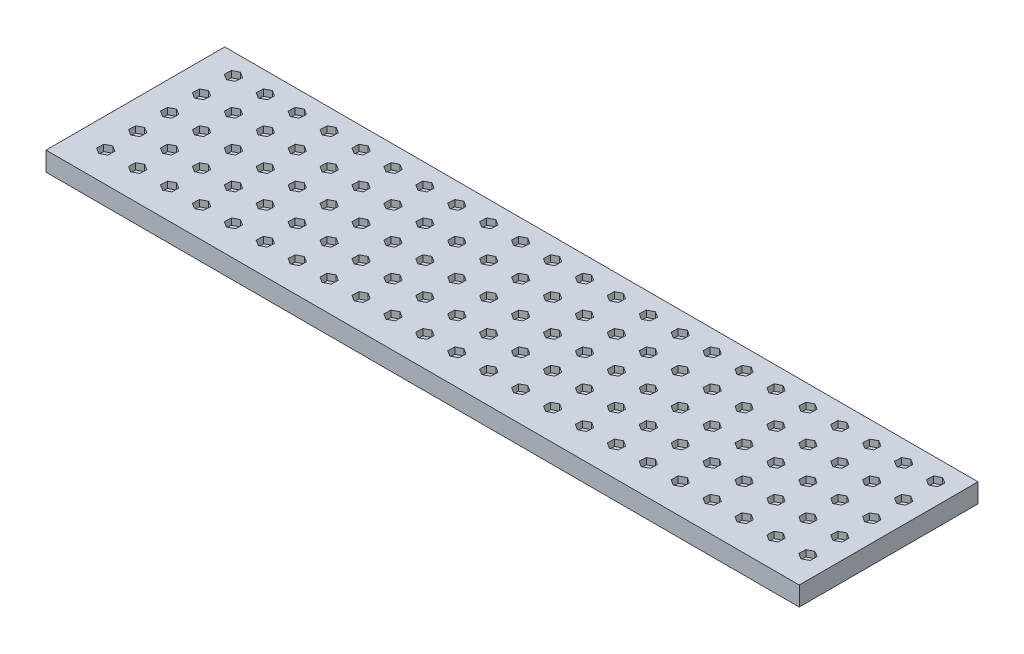
SolidWorks part; units mm, degrees
ref_plane "Front Plane" through (0, 0, 0) normal (0, 0, 1) x (1, 0, 0)
ref_plane "Top Plane" through (0, 0, 0) normal (0, 1, 0) x (1, 0, 0)
ref_plane "Right Plane" through (0, 0, 0) normal (1, 0, 0) x (0, 0, -1)
sketch "Sketch1" plane through (0, 0, 0) normal (0, 1, 0) x (1, 0, 0)
  line L1 (-118, 28) -> (118, 28)
  line L2 (-118, 28) -> (-118, -28)
  line L3 (-118, -28) -> (118, -28)
  line L4 (118, 28) -> (118, -28)
  line L5 (0, -28) -> (0, 28) construction
  line L6 (-118, 0) -> (118, 0) construction
  point P0 (0, 0)
  dimension "D1" = 236
  dimension "D2" = 56
extrude "Boss-Extrude1" add sketch "Sketch1" along normal blind 6
sketch "Sketch2" plane through (0, 6, 0) normal (0, 1, 0) x (1, 0, 0)
  line L0 (-96.9697, 20.3425) -> (-96.8781, 22.4651)
  line L1 (-106.9697, 20.3425) -> (-106.8781, 22.4651)
  line L2 (-106.8781, 22.4651) -> (-108.6705, 23.6058)
  line L3 (-108.6705, 23.6058) -> (-110.5546, 22.6238)
  line L4 (-110.5546, 22.6238) -> (-110.6462, 20.5011)
  line L5 (-110.6462, 20.5011) -> (-108.8538, 19.3605)
  line L6 (-108.8538, 19.3605) -> (-106.9697, 20.3425)
  line L7 (-96.8781, 22.4651) -> (-98.6705, 23.6058)
  line L8 (-98.6705, 23.6058) -> (-100.5546, 22.6238)
  line L9 (-100.5546, 22.6238) -> (-100.6462, 20.5011)
  line L10 (-100.6462, 20.5011) -> (-98.8538, 19.3605)
  line L11 (-98.8538, 19.3605) -> (-96.9697, 20.3425)
  line L12 (-86.9697, 20.3425) -> (-86.8781, 22.4651)
  line L13 (-86.8781, 22.4651) -> (-88.6705, 23.6058)
  line L14 (-88.6705, 23.6058) -> (-90.5546, 22.6238)
  line L15 (-90.5546, 22.6238) -> (-90.6462, 20.5011)
  line L16 (-90.6462, 20.5011) -> (-88.8538, 19.3605)
  line L17 (-88.8538, 19.3605) -> (-86.9697, 20.3425)
  line L18 (-76.9697, 20.3425) -> (-76.8781, 22.4651)
  line L19 (-76.8781, 22.4651) -> (-78.6705, 23.6058)
  line L20 (-78.6705, 23.6058) -> (-80.5546, 22.6238)
  line L21 (-80.5546, 22.6238) -> (-80.6462, 20.5011)
  line L22 (-80.6462, 20.5011) -> (-78.8538, 19.3605)
  line L23 (-78.8538, 19.3605) -> (-76.9697, 20.3425)
  line L24 (-66.9697, 20.3425) -> (-66.8781, 22.4651)
  line L25 (-66.8781, 22.4651) -> (-68.6705, 23.6058)
  line L26 (-68.6705, 23.6058) -> (-70.5546, 22.6238)
  line L27 (-70.5546, 22.6238) -> (-70.6462, 20.5011)
  line L28 (-70.6462, 20.5011) -> (-68.8538, 19.3605)
  line L29 (-68.8538, 19.3605) -> (-66.9697, 20.3425)
  line L30 (-56.9697, 20.3425) -> (-56.8781, 22.4651)
  line L31 (-56.8781, 22.4651) -> (-58.6705, 23.6058)
  line L32 (-58.6705, 23.6058) -> (-60.5546, 22.6238)
  line L33 (-60.5546, 22.6238) -> (-60.6462, 20.5011)
  line L34 (-60.6462, 20.5011) -> (-58.8538, 19.3605)
  line L35 (-58.8538, 19.3605) -> (-56.9697, 20.3425)
  line L36 (-46.9697, 20.3425) -> (-46.8781, 22.4651)
  line L37 (-46.8781, 22.4651) -> (-48.6705, 23.6058)
  line L38 (-48.6705, 23.6058) -> (-50.5546, 22.6238)
  line L39 (-50.5546, 22.6238) -> (-50.6462, 20.5011)
  line L40 (-50.6462, 20.5011) -> (-48.8538, 19.3605)
  line L41 (-48.8538, 19.3605) -> (-46.9697, 20.3425)
  line L42 (-36.9697, 20.3425) -> (-36.8781, 22.4651)
  line L43 (-36.8781, 22.4651) -> (-38.6705, 23.6058)
  line L44 (-38.6705, 23.6058) -> (-40.5546, 22.6238)
  line L45 (-40.5546, 22.6238) -> (-40.6462, 20.5011)
  line L46 (-40.6462, 20.5011) -> (-38.8538, 19.3605)
  line L47 (-38.8538, 19.3605) -> (-36.9697, 20.3425)
  line L48 (-26.9697, 20.3425) -> (-26.8781, 22.4651)
  line L49 (-26.8781, 22.4651) -> (-28.6705, 23.6058)
  line L50 (-28.6705, 23.6058) -> (-30.5546, 22.6238)
  line L51 (-30.5546, 22.6238) -> (-30.6462, 20.5011)
  line L52 (-30.6462, 20.5011) -> (-28.8538, 19.3605)
  line L53 (-28.8538, 19.3605) -> (-26.9697, 20.3425)
  line L54 (-16.9697, 20.3425) -> (-16.8781, 22.4651)
  line L55 (-16.8781, 22.4651) -> (-18.6705, 23.6058)
  line L56 (-18.6705, 23.6058) -> (-20.5546, 22.6238)
  line L57 (-20.5546, 22.6238) -> (-20.6462, 20.5011)
  line L58 (-20.6462, 20.5011) -> (-18.8538, 19.3605)
  line L59 (-18.8538, 19.3605) -> (-16.9697, 20.3425)
  line L60 (-6.9697, 20.3425) -> (-6.8781, 22.4651)
  line L61 (-6.8781, 22.4651) -> (-8.6705, 23.6058)
  line L62 (-8.6705, 23.6058) -> (-10.5546, 22.6238)
  line L63 (-10.5546, 22.6238) -> (-10.6462, 20.5011)
  line L64 (-10.6462, 20.5011) -> (-8.8538, 19.3605)
  line L65 (-8.8538, 19.3605) -> (-6.9697, 20.3425)
  line L66 (3.0303, 20.3425) -> (3.1219, 22.4651)
  line L67 (3.1219, 22.4651) -> (1.3295, 23.6058)
  line L68 (1.3295, 23.6058) -> (-0.5546, 22.6238)
  line L69 (-0.5546, 22.6238) -> (-0.6462, 20.5011)
  line L70 (-0.6462, 20.5011) -> (1.1462, 19.3605)
  line L71 (1.1462, 19.3605) -> (3.0303, 20.3425)
  line L72 (13.0303, 20.3425) -> (13.1219, 22.4651)
  line L73 (13.1219, 22.4651) -> (11.3295, 23.6058)
  line L74 (11.3295, 23.6058) -> (9.4454, 22.6238)
  line L75 (9.4454, 22.6238) -> (9.3538, 20.5011)
  line L76 (9.3538, 20.5011) -> (11.1462, 19.3605)
  line L77 (11.1462, 19.3605) -> (13.0303, 20.3425)
  line L78 (23.0303, 20.3425) -> (23.1219, 22.4651)
  line L79 (23.1219, 22.4651) -> (21.3295, 23.6058)
  line L80 (21.3295, 23.6058) -> (19.4454, 22.6238)
  line L81 (19.4454, 22.6238) -> (19.3538, 20.5011)
  line L82 (19.3538, 20.5011) -> (21.1462, 19.3605)
  line L83 (21.1462, 19.3605) -> (23.0303, 20.3425)
  line L84 (33.0303, 20.3425) -> (33.1219, 22.4651)
  line L85 (33.1219, 22.4651) -> (31.3295, 23.6058)
  line L86 (31.3295, 23.6058) -> (29.4454, 22.6238)
  line L87 (29.4454, 22.6238) -> (29.3538, 20.5011)
  line L88 (29.3538, 20.5011) -> (31.1462, 19.3605)
  line L89 (31.1462, 19.3605) -> (33.0303, 20.3425)
  line L90 (43.0303, 20.3425) -> (43.1219, 22.4651)
  line L91 (43.1219, 22.4651) -> (41.3295, 23.6058)
  line L92 (41.3295, 23.6058) -> (39.4454, 22.6238)
  line L93 (39.4454, 22.6238) -> (39.3538, 20.5011)
  line L94 (39.3538, 20.5011) -> (41.1462, 19.3605)
  line L95 (41.1462, 19.3605) -> (43.0303, 20.3425)
  line L96 (53.0303, 20.3425) -> (53.1219, 22.4651)
  line L97 (53.1219, 22.4651) -> (51.3295, 23.6058)
  line L98 (51.3295, 23.6058) -> (49.4454, 22.6238)
  line L99 (49.4454, 22.6238) -> (49.3538, 20.5011)
  line L100 (49.3538, 20.5011) -> (51.1462, 19.3605)
  line L101 (51.1462, 19.3605) -> (53.0303, 20.3425)
  line L102 (63.0303, 20.3425) -> (63.1219, 22.4651)
  line L103 (63.1219, 22.4651) -> (61.3295, 23.6058)
  line L104 (61.3295, 23.6058) -> (59.4454, 22.6238)
  line L105 (59.4454, 22.6238) -> (59.3538, 20.5011)
  line L106 (59.3538, 20.5011) -> (61.1462, 19.3605)
  line L107 (61.1462, 19.3605) -> (63.0303, 20.3425)
  line L108 (73.0303, 20.3425) -> (73.1219, 22.4651)
  line L109 (73.1219, 22.4651) -> (71.3295, 23.6058)
  line L110 (71.3295, 23.6058) -> (69.4454, 22.6238)
  line L111 (69.4454, 22.6238) -> (69.3538, 20.5011)
  line L112 (69.3538, 20.5011) -> (71.1462, 19.3605)
  line L113 (71.1462, 19.3605) -> (73.0303, 20.3425)
  line L114 (83.0303, 20.3425) -> (83.1219, 22.4651)
  line L115 (83.1219, 22.4651) -> (81.3295, 23.6058)
  line L116 (81.3295, 23.6058) -> (79.4454, 22.6238)
  line L117 (79.4454, 22.6238) -> (79.3538, 20.5011)
  line L118 (79.3538, 20.5011) -> (81.1462, 19.3605)
  line L119 (81.1462, 19.3605) -> (83.0303, 20.3425)
  line L120 (93.0303, 20.3425) -> (93.1219, 22.4651)
  line L121 (93.1219, 22.4651) -> (91.3295, 23.6058)
  line L122 (91.3295, 23.6058) -> (89.4454, 22.6238)
  line L123 (89.4454, 22.6238) -> (89.3538, 20.5011)
  line L124 (89.3538, 20.5011) -> (91.1462, 19.3605)
  line L125 (91.1462, 19.3605) -> (93.0303, 20.3425)
  line L126 (103.0303, 20.3425) -> (103.1219, 22.4651)
  line L127 (103.1219, 22.4651) -> (101.3295, 23.6058)
  line L128 (101.3295, 23.6058) -> (99.4454, 22.6238)
  line L129 (99.4454, 22.6238) -> (99.3538, 20.5011)
  line L130 (99.3538, 20.5011) -> (101.1462, 19.3605)
  line L131 (101.1462, 19.3605) -> (103.0303, 20.3425)
  line L132 (113.0303, 20.3425) -> (113.1219, 22.4651)
  line L133 (113.1219, 22.4651) -> (111.3295, 23.6058)
  line L134 (111.3295, 23.6058) -> (109.4454, 22.6238)
  line L135 (109.4454, 22.6238) -> (109.3538, 20.5011)
  line L136 (109.3538, 20.5011) -> (111.1462, 19.3605)
  line L137 (111.1462, 19.3605) -> (113.0303, 20.3425)
  line L138 (-96.9697, 10.3425) -> (-96.8781, 12.4651)
  line L139 (-96.8781, 12.4651) -> (-98.6705, 13.6058)
  line L140 (-98.6705, 13.6058) -> (-100.5546, 12.6238)
  line L141 (-100.5546, 12.6238) -> (-100.6462, 10.5011)
  line L142 (-100.6462, 10.5011) -> (-98.8538, 9.3605)
  line L143 (-98.8538, 9.3605) -> (-96.9697, 10.3425)
  line L144 (-86.9697, 10.3425) -> (-86.8781, 12.4651)
  line L145 (-86.8781, 12.4651) -> (-88.6705, 13.6058)
  line L146 (-88.6705, 13.6058) -> (-90.5546, 12.6238)
  line L147 (-90.5546, 12.6238) -> (-90.6462, 10.5011)
  line L148 (-90.6462, 10.5011) -> (-88.8538, 9.3605)
  line L149 (-88.8538, 9.3605) -> (-86.9697, 10.3425)
  line L150 (-76.9697, 10.3425) -> (-76.8781, 12.4651)
  line L151 (-76.8781, 12.4651) -> (-78.6705, 13.6058)
  line L152 (-78.6705, 13.6058) -> (-80.5546, 12.6238)
  line L153 (-80.5546, 12.6238) -> (-80.6462, 10.5011)
  line L154 (-80.6462, 10.5011) -> (-78.8538, 9.3605)
  line L155 (-78.8538, 9.3605) -> (-76.9697, 10.3425)
  line L156 (-66.9697, 10.3425) -> (-66.8781, 12.4651)
  line L157 (-66.8781, 12.4651) -> (-68.6705, 13.6058)
  line L158 (-68.6705, 13.6058) -> (-70.5546, 12.6238)
  line L159 (-70.5546, 12.6238) -> (-70.6462, 10.5011)
  line L160 (-70.6462, 10.5011) -> (-68.8538, 9.3605)
  line L161 (-68.8538, 9.3605) -> (-66.9697, 10.3425)
  line L162 (-56.9697, 10.3425) -> (-56.8781, 12.4651)
  line L163 (-56.8781, 12.4651) -> (-58.6705, 13.6058)
  line L164 (-58.6705, 13.6058) -> (-60.5546, 12.6238)
  line L165 (-60.5546, 12.6238) -> (-60.6462, 10.5011)
  line L166 (-60.6462, 10.5011) -> (-58.8538, 9.3605)
  line L167 (-58.8538, 9.3605) -> (-56.9697, 10.3425)
  line L168 (-46.9697, 10.3425) -> (-46.8781, 12.4651)
  line L169 (-46.8781, 12.4651) -> (-48.6705, 13.6058)
  line L170 (-48.6705, 13.6058) -> (-50.5546, 12.6238)
  line L171 (-50.5546, 12.6238) -> (-50.6462, 10.5011)
  line L172 (-50.6462, 10.5011) -> (-48.8538, 9.3605)
  line L173 (-48.8538, 9.3605) -> (-46.9697, 10.3425)
  line L174 (-36.9697, 10.3425) -> (-36.8781, 12.4651)
  line L175 (-36.8781, 12.4651) -> (-38.6705, 13.6058)
  line L176 (-38.6705, 13.6058) -> (-40.5546, 12.6238)
  line L177 (-40.5546, 12.6238) -> (-40.6462, 10.5011)
  line L178 (-40.6462, 10.5011) -> (-38.8538, 9.3605)
  line L179 (-38.8538, 9.3605) -> (-36.9697, 10.3425)
  line L180 (-26.9697, 10.3425) -> (-26.8781, 12.4651)
  line L181 (-26.8781, 12.4651) -> (-28.6705, 13.6058)
  line L182 (-28.6705, 13.6058) -> (-30.5546, 12.6238)
  line L183 (-30.5546, 12.6238) -> (-30.6462, 10.5011)
  line L184 (-30.6462, 10.5011) -> (-28.8538, 9.3605)
  line L185 (-28.8538, 9.3605) -> (-26.9697, 10.3425)
  line L186 (-16.9697, 10.3425) -> (-16.8781, 12.4651)
  line L187 (-16.8781, 12.4651) -> (-18.6705, 13.6058)
  line L188 (-18.6705, 13.6058) -> (-20.5546, 12.6238)
  line L189 (-20.5546, 12.6238) -> (-20.6462, 10.5011)
  line L190 (-20.6462, 10.5011) -> (-18.8538, 9.3605)
  line L191 (-18.8538, 9.3605) -> (-16.9697, 10.3425)
  line L192 (-6.9697, 10.3425) -> (-6.8781, 12.4651)
  line L193 (-6.8781, 12.4651) -> (-8.6705, 13.6058)
  line L194 (-8.6705, 13.6058) -> (-10.5546, 12.6238)
  line L195 (-10.5546, 12.6238) -> (-10.6462, 10.5011)
  line L196 (-10.6462, 10.5011) -> (-8.8538, 9.3605)
  line L197 (-8.8538, 9.3605) -> (-6.9697, 10.3425)
  line L198 (3.0303, 10.3425) -> (3.1219, 12.4651)
  line L199 (3.1219, 12.4651) -> (1.3295, 13.6058)
  line L200 (1.3295, 13.6058) -> (-0.5546, 12.6238)
  line L201 (-0.5546, 12.6238) -> (-0.6462, 10.5011)
  line L202 (-0.6462, 10.5011) -> (1.1462, 9.3605)
  line L203 (1.1462, 9.3605) -> (3.0303, 10.3425)
  line L204 (13.0303, 10.3425) -> (13.1219, 12.4651)
  line L205 (13.1219, 12.4651) -> (11.3295, 13.6058)
  line L206 (11.3295, 13.6058) -> (9.4454, 12.6238)
  line L207 (9.4454, 12.6238) -> (9.3538, 10.5011)
  line L208 (9.3538, 10.5011) -> (11.1462, 9.3605)
  line L209 (11.1462, 9.3605) -> (13.0303, 10.3425)
  line L210 (23.0303, 10.3425) -> (23.1219, 12.4651)
  line L211 (23.1219, 12.4651) -> (21.3295, 13.6058)
  line L212 (21.3295, 13.6058) -> (19.4454, 12.6238)
  line L213 (19.4454, 12.6238) -> (19.3538, 10.5011)
  line L214 (19.3538, 10.5011) -> (21.1462, 9.3605)
  line L215 (21.1462, 9.3605) -> (23.0303, 10.3425)
  line L216 (33.0303, 10.3425) -> (33.1219, 12.4651)
  line L217 (33.1219, 12.4651) -> (31.3295, 13.6058)
  line L218 (31.3295, 13.6058) -> (29.4454, 12.6238)
  line L219 (29.4454, 12.6238) -> (29.3538, 10.5011)
  line L220 (29.3538, 10.5011) -> (31.1462, 9.3605)
  line L221 (31.1462, 9.3605) -> (33.0303, 10.3425)
  line L222 (43.0303, 10.3425) -> (43.1219, 12.4651)
  line L223 (43.1219, 12.4651) -> (41.3295, 13.6058)
  line L224 (41.3295, 13.6058) -> (39.4454, 12.6238)
  line L225 (39.4454, 12.6238) -> (39.3538, 10.5011)
  line L226 (39.3538, 10.5011) -> (41.1462, 9.3605)
  line L227 (41.1462, 9.3605) -> (43.0303, 10.3425)
  line L228 (53.0303, 10.3425) -> (53.1219, 12.4651)
  line L229 (53.1219, 12.4651) -> (51.3295, 13.6058)
  line L230 (51.3295, 13.6058) -> (49.4454, 12.6238)
  line L231 (49.4454, 12.6238) -> (49.3538, 10.5011)
  line L232 (49.3538, 10.5011) -> (51.1462, 9.3605)
  line L233 (51.1462, 9.3605) -> (53.0303, 10.3425)
  line L234 (63.0303, 10.3425) -> (63.1219, 12.4651)
  line L235 (63.1219, 12.4651) -> (61.3295, 13.6058)
  line L236 (61.3295, 13.6058) -> (59.4454, 12.6238)
  line L237 (59.4454, 12.6238) -> (59.3538, 10.5011)
  line L238 (59.3538, 10.5011) -> (61.1462, 9.3605)
  line L239 (61.1462, 9.3605) -> (63.0303, 10.3425)
  line L240 (73.0303, 10.3425) -> (73.1219, 12.4651)
  line L241 (73.1219, 12.4651) -> (71.3295, 13.6058)
  line L242 (71.3295, 13.6058) -> (69.4454, 12.6238)
  line L243 (69.4454, 12.6238) -> (69.3538, 10.5011)
  line L244 (69.3538, 10.5011) -> (71.1462, 9.3605)
  line L245 (71.1462, 9.3605) -> (73.0303, 10.3425)
  line L246 (83.0303, 10.3425) -> (83.1219, 12.4651)
  line L247 (83.1219, 12.4651) -> (81.3295, 13.6058)
  line L248 (81.3295, 13.6058) -> (79.4454, 12.6238)
  line L249 (79.4454, 12.6238) -> (79.3538, 10.5011)
  line L250 (79.3538, 10.5011) -> (81.1462, 9.3605)
  line L251 (81.1462, 9.3605) -> (83.0303, 10.3425)
  line L252 (93.0303, 10.3425) -> (93.1219, 12.4651)
  line L253 (93.1219, 12.4651) -> (91.3295, 13.6058)
  line L254 (91.3295, 13.6058) -> (89.4454, 12.6238)
  line L255 (89.4454, 12.6238) -> (89.3538, 10.5011)
  line L256 (89.3538, 10.5011) -> (91.1462, 9.3605)
  line L257 (91.1462, 9.3605) -> (93.0303, 10.3425)
  line L258 (103.0303, 10.3425) -> (103.1219, 12.4651)
  line L259 (103.1219, 12.4651) -> (101.3295, 13.6058)
  line L260 (101.3295, 13.6058) -> (99.4454, 12.6238)
  line L261 (99.4454, 12.6238) -> (99.3538, 10.5011)
  line L262 (99.3538, 10.5011) -> (101.1462, 9.3605)
  line L263 (101.1462, 9.3605) -> (103.0303, 10.3425)
  line L264 (113.0303, 10.3425) -> (113.1219, 12.4651)
  line L265 (113.1219, 12.4651) -> (111.3295, 13.6058)
  line L266 (111.3295, 13.6058) -> (109.4454, 12.6238)
  line L267 (109.4454, 12.6238) -> (109.3538, 10.5011)
  line L268 (109.3538, 10.5011) -> (111.1462, 9.3605)
  line L269 (111.1462, 9.3605) -> (113.0303, 10.3425)
  line L270 (-96.9697, 0.3425) -> (-96.8781, 2.4651)
  line L271 (-96.8781, 2.4651) -> (-98.6705, 3.6058)
  line L272 (-98.6705, 3.6058) -> (-100.5546, 2.6238)
  line L273 (-100.5546, 2.6238) -> (-100.6462, 0.5011)
  line L274 (-100.6462, 0.5011) -> (-98.8538, -0.6395)
  line L275 (-98.8538, -0.6395) -> (-96.9697, 0.3425)
  line L276 (-86.9697, 0.3425) -> (-86.8781, 2.4651)
  line L277 (-86.8781, 2.4651) -> (-88.6705, 3.6058)
  line L278 (-88.6705, 3.6058) -> (-90.5546, 2.6238)
  line L279 (-90.5546, 2.6238) -> (-90.6462, 0.5011)
  line L280 (-90.6462, 0.5011) -> (-88.8538, -0.6395)
  line L281 (-88.8538, -0.6395) -> (-86.9697, 0.3425)
  line L282 (-76.9697, 0.3425) -> (-76.8781, 2.4651)
  line L283 (-76.8781, 2.4651) -> (-78.6705, 3.6058)
  line L284 (-78.6705, 3.6058) -> (-80.5546, 2.6238)
  line L285 (-80.5546, 2.6238) -> (-80.6462, 0.5011)
  line L286 (-80.6462, 0.5011) -> (-78.8538, -0.6395)
  line L287 (-78.8538, -0.6395) -> (-76.9697, 0.3425)
  line L288 (-66.9697, 0.3425) -> (-66.8781, 2.4651)
  line L289 (-66.8781, 2.4651) -> (-68.6705, 3.6058)
  line L290 (-68.6705, 3.6058) -> (-70.5546, 2.6238)
  line L291 (-70.5546, 2.6238) -> (-70.6462, 0.5011)
  line L292 (-70.6462, 0.5011) -> (-68.8538, -0.6395)
  line L293 (-68.8538, -0.6395) -> (-66.9697, 0.3425)
  line L294 (-56.9697, 0.3425) -> (-56.8781, 2.4651)
  line L295 (-56.8781, 2.4651) -> (-58.6705, 3.6058)
  line L296 (-58.6705, 3.6058) -> (-60.5546, 2.6238)
  line L297 (-60.5546, 2.6238) -> (-60.6462, 0.5011)
  line L298 (-60.6462, 0.5011) -> (-58.8538, -0.6395)
  line L299 (-58.8538, -0.6395) -> (-56.9697, 0.3425)
  line L300 (-46.9697, 0.3425) -> (-46.8781, 2.4651)
  line L301 (-46.8781, 2.4651) -> (-48.6705, 3.6058)
  line L302 (-48.6705, 3.6058) -> (-50.5546, 2.6238)
  line L303 (-50.5546, 2.6238) -> (-50.6462, 0.5011)
  line L304 (-50.6462, 0.5011) -> (-48.8538, -0.6395)
  line L305 (-48.8538, -0.6395) -> (-46.9697, 0.3425)
  line L306 (-36.9697, 0.3425) -> (-36.8781, 2.4651)
  line L307 (-36.8781, 2.4651) -> (-38.6705, 3.6058)
  line L308 (-38.6705, 3.6058) -> (-40.5546, 2.6238)
  line L309 (-40.5546, 2.6238) -> (-40.6462, 0.5011)
  line L310 (-40.6462, 0.5011) -> (-38.8538, -0.6395)
  line L311 (-38.8538, -0.6395) -> (-36.9697, 0.3425)
  line L312 (-26.9697, 0.3425) -> (-26.8781, 2.4651)
  line L313 (-26.8781, 2.4651) -> (-28.6705, 3.6058)
  line L314 (-28.6705, 3.6058) -> (-30.5546, 2.6238)
  line L315 (-30.5546, 2.6238) -> (-30.6462, 0.5011)
  line L316 (-30.6462, 0.5011) -> (-28.8538, -0.6395)
  line L317 (-28.8538, -0.6395) -> (-26.9697, 0.3425)
  line L318 (-16.9697, 0.3425) -> (-16.8781, 2.4651)
  line L319 (-16.8781, 2.4651) -> (-18.6705, 3.6058)
  line L320 (-18.6705, 3.6058) -> (-20.5546, 2.6238)
  line L321 (-20.5546, 2.6238) -> (-20.6462, 0.5011)
  line L322 (-20.6462, 0.5011) -> (-18.8538, -0.6395)
  line L323 (-18.8538, -0.6395) -> (-16.9697, 0.3425)
  line L324 (-6.9697, 0.3425) -> (-6.8781, 2.4651)
  line L325 (-6.8781, 2.4651) -> (-8.6705, 3.6058)
  line L326 (-8.6705, 3.6058) -> (-10.5546, 2.6238)
  line L327 (-10.5546, 2.6238) -> (-10.6462, 0.5011)
  line L328 (-10.6462, 0.5011) -> (-8.8538, -0.6395)
  line L329 (-8.8538, -0.6395) -> (-6.9697, 0.3425)
  line L330 (3.0303, 0.3425) -> (3.1219, 2.4651)
  line L331 (3.1219, 2.4651) -> (1.3295, 3.6058)
  line L332 (1.3295, 3.6058) -> (-0.5546, 2.6238)
  line L333 (-0.5546, 2.6238) -> (-0.6462, 0.5011)
  line L334 (-0.6462, 0.5011) -> (1.1462, -0.6395)
  line L335 (1.1462, -0.6395) -> (3.0303, 0.3425)
  line L336 (13.0303, 0.3425) -> (13.1219, 2.4651)
  line L337 (13.1219, 2.4651) -> (11.3295, 3.6058)
  line L338 (11.3295, 3.6058) -> (9.4454, 2.6238)
  line L339 (9.4454, 2.6238) -> (9.3538, 0.5011)
  line L340 (9.3538, 0.5011) -> (11.1462, -0.6395)
  line L341 (11.1462, -0.6395) -> (13.0303, 0.3425)
  line L342 (23.0303, 0.3425) -> (23.1219, 2.4651)
  line L343 (23.1219, 2.4651) -> (21.3295, 3.6058)
  line L344 (21.3295, 3.6058) -> (19.4454, 2.6238)
  line L345 (19.4454, 2.6238) -> (19.3538, 0.5011)
  line L346 (19.3538, 0.5011) -> (21.1462, -0.6395)
  line L347 (21.1462, -0.6395) -> (23.0303, 0.3425)
  line L348 (33.0303, 0.3425) -> (33.1219, 2.4651)
  line L349 (33.1219, 2.4651) -> (31.3295, 3.6058)
  line L350 (31.3295, 3.6058) -> (29.4454, 2.6238)
  line L351 (29.4454, 2.6238) -> (29.3538, 0.5011)
  line L352 (29.3538, 0.5011) -> (31.1462, -0.6395)
  line L353 (31.1462, -0.6395) -> (33.0303, 0.3425)
  line L354 (43.0303, 0.3425) -> (43.1219, 2.4651)
  line L355 (43.1219, 2.4651) -> (41.3295, 3.6058)
  line L356 (41.3295, 3.6058) -> (39.4454, 2.6238)
  line L357 (39.4454, 2.6238) -> (39.3538, 0.5011)
  line L358 (39.3538, 0.5011) -> (41.1462, -0.6395)
  line L359 (41.1462, -0.6395) -> (43.0303, 0.3425)
  line L360 (53.0303, 0.3425) -> (53.1219, 2.4651)
  line L361 (53.1219, 2.4651) -> (51.3295, 3.6058)
  line L362 (51.3295, 3.6058) -> (49.4454, 2.6238)
  line L363 (49.4454, 2.6238) -> (49.3538, 0.5011)
  line L364 (49.3538, 0.5011) -> (51.1462, -0.6395)
  line L365 (51.1462, -0.6395) -> (53.0303, 0.3425)
  line L366 (63.0303, 0.3425) -> (63.1219, 2.4651)
  line L367 (63.1219, 2.4651) -> (61.3295, 3.6058)
  line L368 (61.3295, 3.6058) -> (59.4454, 2.6238)
  line L369 (59.4454, 2.6238) -> (59.3538, 0.5011)
  line L370 (59.3538, 0.5011) -> (61.1462, -0.6395)
  line L371 (61.1462, -0.6395) -> (63.0303, 0.3425)
  line L372 (73.0303, 0.3425) -> (73.1219, 2.4651)
  line L373 (73.1219, 2.4651) -> (71.3295, 3.6058)
  line L374 (71.3295, 3.6058) -> (69.4454, 2.6238)
  line L375 (69.4454, 2.6238) -> (69.3538, 0.5011)
  line L376 (69.3538, 0.5011) -> (71.1462, -0.6395)
  line L377 (71.1462, -0.6395) -> (73.0303, 0.3425)
  line L378 (83.0303, 0.3425) -> (83.1219, 2.4651)
  line L379 (83.1219, 2.4651) -> (81.3295, 3.6058)
  line L380 (81.3295, 3.6058) -> (79.4454, 2.6238)
  line L381 (79.4454, 2.6238) -> (79.3538, 0.5011)
  line L382 (79.3538, 0.5011) -> (81.1462, -0.6395)
  line L383 (81.1462, -0.6395) -> (83.0303, 0.3425)
  line L384 (93.0303, 0.3425) -> (93.1219, 2.4651)
  line L385 (93.1219, 2.4651) -> (91.3295, 3.6058)
  line L386 (91.3295, 3.6058) -> (89.4454, 2.6238)
  line L387 (89.4454, 2.6238) -> (89.3538, 0.5011)
  line L388 (89.3538, 0.5011) -> (91.1462, -0.6395)
  line L389 (91.1462, -0.6395) -> (93.0303, 0.3425)
  line L390 (103.0303, 0.3425) -> (103.1219, 2.4651)
  line L391 (103.1219, 2.4651) -> (101.3295, 3.6058)
  line L392 (101.3295, 3.6058) -> (99.4454, 2.6238)
  line L393 (99.4454, 2.6238) -> (99.3538, 0.5011)
  line L394 (99.3538, 0.5011) -> (101.1462, -0.6395)
  line L395 (101.1462, -0.6395) -> (103.0303, 0.3425)
  line L396 (113.0303, 0.3425) -> (113.1219, 2.4651)
  line L397 (113.1219, 2.4651) -> (111.3295, 3.6058)
  line L398 (111.3295, 3.6058) -> (109.4454, 2.6238)
  line L399 (109.4454, 2.6238) -> (109.3538, 0.5011)
  line L400 (109.3538, 0.5011) -> (111.1462, -0.6395)
  line L401 (111.1462, -0.6395) -> (113.0303, 0.3425)
  line L402 (-96.9697, -9.6575) -> (-96.8781, -7.5349)
  line L403 (-96.8781, -7.5349) -> (-98.6705, -6.3942)
  line L404 (-98.6705, -6.3942) -> (-100.5546, -7.3762)
  line L405 (-100.5546, -7.3762) -> (-100.6462, -9.4989)
  line L406 (-100.6462, -9.4989) -> (-98.8538, -10.6395)
  line L407 (-98.8538, -10.6395) -> (-96.9697, -9.6575)
  line L408 (-86.9697, -9.6575) -> (-86.8781, -7.5349)
  line L409 (-86.8781, -7.5349) -> (-88.6705, -6.3942)
  line L410 (-88.6705, -6.3942) -> (-90.5546, -7.3762)
  line L411 (-90.5546, -7.3762) -> (-90.6462, -9.4989)
  line L412 (-90.6462, -9.4989) -> (-88.8538, -10.6395)
  line L413 (-88.8538, -10.6395) -> (-86.9697, -9.6575)
  line L414 (-76.9697, -9.6575) -> (-76.8781, -7.5349)
  line L415 (-76.8781, -7.5349) -> (-78.6705, -6.3942)
  line L416 (-78.6705, -6.3942) -> (-80.5546, -7.3762)
  line L417 (-80.5546, -7.3762) -> (-80.6462, -9.4989)
  line L418 (-80.6462, -9.4989) -> (-78.8538, -10.6395)
  line L419 (-78.8538, -10.6395) -> (-76.9697, -9.6575)
  line L420 (-66.9697, -9.6575) -> (-66.8781, -7.5349)
  line L421 (-66.8781, -7.5349) -> (-68.6705, -6.3942)
  line L422 (-68.6705, -6.3942) -> (-70.5546, -7.3762)
  line L423 (-70.5546, -7.3762) -> (-70.6462, -9.4989)
  line L424 (-70.6462, -9.4989) -> (-68.8538, -10.6395)
  line L425 (-68.8538, -10.6395) -> (-66.9697, -9.6575)
  line L426 (-56.9697, -9.6575) -> (-56.8781, -7.5349)
  line L427 (-56.8781, -7.5349) -> (-58.6705, -6.3942)
  line L428 (-58.6705, -6.3942) -> (-60.5546, -7.3762)
  line L429 (-60.5546, -7.3762) -> (-60.6462, -9.4989)
  line L430 (-60.6462, -9.4989) -> (-58.8538, -10.6395)
  line L431 (-58.8538, -10.6395) -> (-56.9697, -9.6575)
  line L432 (-46.9697, -9.6575) -> (-46.8781, -7.5349)
  line L433 (-46.8781, -7.5349) -> (-48.6705, -6.3942)
  line L434 (-48.6705, -6.3942) -> (-50.5546, -7.3762)
  line L435 (-50.5546, -7.3762) -> (-50.6462, -9.4989)
  line L436 (-50.6462, -9.4989) -> (-48.8538, -10.6395)
  line L437 (-48.8538, -10.6395) -> (-46.9697, -9.6575)
  line L438 (-36.9697, -9.6575) -> (-36.8781, -7.5349)
  line L439 (-36.8781, -7.5349) -> (-38.6705, -6.3942)
  line L440 (-38.6705, -6.3942) -> (-40.5546, -7.3762)
  line L441 (-40.5546, -7.3762) -> (-40.6462, -9.4989)
  line L442 (-40.6462, -9.4989) -> (-38.8538, -10.6395)
  line L443 (-38.8538, -10.6395) -> (-36.9697, -9.6575)
  line L444 (-26.9697, -9.6575) -> (-26.8781, -7.5349)
  line L445 (-26.8781, -7.5349) -> (-28.6705, -6.3942)
  line L446 (-28.6705, -6.3942) -> (-30.5546, -7.3762)
  line L447 (-30.5546, -7.3762) -> (-30.6462, -9.4989)
  line L448 (-30.6462, -9.4989) -> (-28.8538, -10.6395)
  line L449 (-28.8538, -10.6395) -> (-26.9697, -9.6575)
  line L450 (-16.9697, -9.6575) -> (-16.8781, -7.5349)
  line L451 (-16.8781, -7.5349) -> (-18.6705, -6.3942)
  line L452 (-18.6705, -6.3942) -> (-20.5546, -7.3762)
  line L453 (-20.5546, -7.3762) -> (-20.6462, -9.4989)
  line L454 (-20.6462, -9.4989) -> (-18.8538, -10.6395)
  line L455 (-18.8538, -10.6395) -> (-16.9697, -9.6575)
  line L456 (-6.9697, -9.6575) -> (-6.8781, -7.5349)
  line L457 (-6.8781, -7.5349) -> (-8.6705, -6.3942)
  line L458 (-8.6705, -6.3942) -> (-10.5546, -7.3762)
  line L459 (-10.5546, -7.3762) -> (-10.6462, -9.4989)
  line L460 (-10.6462, -9.4989) -> (-8.8538, -10.6395)
  line L461 (-8.8538, -10.6395) -> (-6.9697, -9.6575)
  line L462 (3.0303, -9.6575) -> (3.1219, -7.5349)
  line L463 (3.1219, -7.5349) -> (1.3295, -6.3942)
  line L464 (1.3295, -6.3942) -> (-0.5546, -7.3762)
  line L465 (-0.5546, -7.3762) -> (-0.6462, -9.4989)
  line L466 (-0.6462, -9.4989) -> (1.1462, -10.6395)
  line L467 (1.1462, -10.6395) -> (3.0303, -9.6575)
  line L468 (13.0303, -9.6575) -> (13.1219, -7.5349)
  line L469 (13.1219, -7.5349) -> (11.3295, -6.3942)
  line L470 (11.3295, -6.3942) -> (9.4454, -7.3762)
  line L471 (9.4454, -7.3762) -> (9.3538, -9.4989)
  line L472 (9.3538, -9.4989) -> (11.1462, -10.6395)
  line L473 (11.1462, -10.6395) -> (13.0303, -9.6575)
  line L474 (23.0303, -9.6575) -> (23.1219, -7.5349)
  line L475 (23.1219, -7.5349) -> (21.3295, -6.3942)
  line L476 (21.3295, -6.3942) -> (19.4454, -7.3762)
  line L477 (19.4454, -7.3762) -> (19.3538, -9.4989)
  line L478 (19.3538, -9.4989) -> (21.1462, -10.6395)
  line L479 (21.1462, -10.6395) -> (23.0303, -9.6575)
  line L480 (33.0303, -9.6575) -> (33.1219, -7.5349)
  line L481 (33.1219, -7.5349) -> (31.3295, -6.3942)
  line L482 (31.3295, -6.3942) -> (29.4454, -7.3762)
  line L483 (29.4454, -7.3762) -> (29.3538, -9.4989)
  line L484 (29.3538, -9.4989) -> (31.1462, -10.6395)
  line L485 (31.1462, -10.6395) -> (33.0303, -9.6575)
  line L486 (43.0303, -9.6575) -> (43.1219, -7.5349)
  line L487 (43.1219, -7.5349) -> (41.3295, -6.3942)
  line L488 (41.3295, -6.3942) -> (39.4454, -7.3762)
  line L489 (39.4454, -7.3762) -> (39.3538, -9.4989)
  line L490 (39.3538, -9.4989) -> (41.1462, -10.6395)
  line L491 (41.1462, -10.6395) -> (43.0303, -9.6575)
  line L492 (53.0303, -9.6575) -> (53.1219, -7.5349)
  line L493 (53.1219, -7.5349) -> (51.3295, -6.3942)
  line L494 (51.3295, -6.3942) -> (49.4454, -7.3762)
  line L495 (49.4454, -7.3762) -> (49.3538, -9.4989)
  line L496 (49.3538, -9.4989) -> (51.1462, -10.6395)
  line L497 (51.1462, -10.6395) -> (53.0303, -9.6575)
  line L498 (63.0303, -9.6575) -> (63.1219, -7.5349)
  line L499 (63.1219, -7.5349) -> (61.3295, -6.3942)
  line L500 (61.3295, -6.3942) -> (59.4454, -7.3762)
  line L501 (59.4454, -7.3762) -> (59.3538, -9.4989)
  line L502 (59.3538, -9.4989) -> (61.1462, -10.6395)
  line L503 (61.1462, -10.6395) -> (63.0303, -9.6575)
  line L504 (73.0303, -9.6575) -> (73.1219, -7.5349)
  line L505 (73.1219, -7.5349) -> (71.3295, -6.3942)
  line L506 (71.3295, -6.3942) -> (69.4454, -7.3762)
  line L507 (69.4454, -7.3762) -> (69.3538, -9.4989)
  line L508 (69.3538, -9.4989) -> (71.1462, -10.6395)
  line L509 (71.1462, -10.6395) -> (73.0303, -9.6575)
  line L510 (83.0303, -9.6575) -> (83.1219, -7.5349)
  line L511 (83.1219, -7.5349) -> (81.3295, -6.3942)
  line L512 (81.3295, -6.3942) -> (79.4454, -7.3762)
  line L513 (79.4454, -7.3762) -> (79.3538, -9.4989)
  line L514 (79.3538, -9.4989) -> (81.1462, -10.6395)
  line L515 (81.1462, -10.6395) -> (83.0303, -9.6575)
  line L516 (93.0303, -9.6575) -> (93.1219, -7.5349)
  line L517 (93.1219, -7.5349) -> (91.3295, -6.3942)
  line L518 (91.3295, -6.3942) -> (89.4454, -7.3762)
  line L519 (89.4454, -7.3762) -> (89.3538, -9.4989)
  line L520 (89.3538, -9.4989) -> (91.1462, -10.6395)
  line L521 (91.1462, -10.6395) -> (93.0303, -9.6575)
  line L522 (103.0303, -9.6575) -> (103.1219, -7.5349)
  line L523 (103.1219, -7.5349) -> (101.3295, -6.3942)
  line L524 (101.3295, -6.3942) -> (99.4454, -7.3762)
  line L525 (99.4454, -7.3762) -> (99.3538, -9.4989)
  line L526 (99.3538, -9.4989) -> (101.1462, -10.6395)
  line L527 (101.1462, -10.6395) -> (103.0303, -9.6575)
  line L528 (113.0303, -9.6575) -> (113.1219, -7.5349)
  line L529 (113.1219, -7.5349) -> (111.3295, -6.3942)
  line L530 (111.3295, -6.3942) -> (109.4454, -7.3762)
  line L531 (109.4454, -7.3762) -> (109.3538, -9.4989)
  line L532 (109.3538, -9.4989) -> (111.1462, -10.6395)
  line L533 (111.1462, -10.6395) -> (113.0303, -9.6575)
  line L534 (-96.9697, -19.6575) -> (-96.8781, -17.5349)
  line L535 (-96.8781, -17.5349) -> (-98.6705, -16.3942)
  line L536 (-98.6705, -16.3942) -> (-100.5546, -17.3762)
  line L537 (-100.5546, -17.3762) -> (-100.6462, -19.4989)
  line L538 (-100.6462, -19.4989) -> (-98.8538, -20.6395)
  line L539 (-98.8538, -20.6395) -> (-96.9697, -19.6575)
  line L540 (-86.9697, -19.6575) -> (-86.8781, -17.5349)
  line L541 (-86.8781, -17.5349) -> (-88.6705, -16.3942)
  line L542 (-88.6705, -16.3942) -> (-90.5546, -17.3762)
  line L543 (-90.5546, -17.3762) -> (-90.6462, -19.4989)
  line L544 (-90.6462, -19.4989) -> (-88.8538, -20.6395)
  line L545 (-88.8538, -20.6395) -> (-86.9697, -19.6575)
  line L546 (-76.9697, -19.6575) -> (-76.8781, -17.5349)
  line L547 (-76.8781, -17.5349) -> (-78.6705, -16.3942)
  line L548 (-78.6705, -16.3942) -> (-80.5546, -17.3762)
  line L549 (-80.5546, -17.3762) -> (-80.6462, -19.4989)
  line L550 (-80.6462, -19.4989) -> (-78.8538, -20.6395)
  line L551 (-78.8538, -20.6395) -> (-76.9697, -19.6575)
  line L552 (-66.9697, -19.6575) -> (-66.8781, -17.5349)
  line L553 (-66.8781, -17.5349) -> (-68.6705, -16.3942)
  line L554 (-68.6705, -16.3942) -> (-70.5546, -17.3762)
  line L555 (-70.5546, -17.3762) -> (-70.6462, -19.4989)
  line L556 (-70.6462, -19.4989) -> (-68.8538, -20.6395)
  line L557 (-68.8538, -20.6395) -> (-66.9697, -19.6575)
  line L558 (-56.9697, -19.6575) -> (-56.8781, -17.5349)
  line L559 (-56.8781, -17.5349) -> (-58.6705, -16.3942)
  line L560 (-58.6705, -16.3942) -> (-60.5546, -17.3762)
  line L561 (-60.5546, -17.3762) -> (-60.6462, -19.4989)
  line L562 (-60.6462, -19.4989) -> (-58.8538, -20.6395)
  line L563 (-58.8538, -20.6395) -> (-56.9697, -19.6575)
  line L564 (-46.9697, -19.6575) -> (-46.8781, -17.5349)
  line L565 (-46.8781, -17.5349) -> (-48.6705, -16.3942)
  line L566 (-48.6705, -16.3942) -> (-50.5546, -17.3762)
  line L567 (-50.5546, -17.3762) -> (-50.6462, -19.4989)
  line L568 (-50.6462, -19.4989) -> (-48.8538, -20.6395)
  line L569 (-48.8538, -20.6395) -> (-46.9697, -19.6575)
  line L570 (-36.9697, -19.6575) -> (-36.8781, -17.5349)
  line L571 (-36.8781, -17.5349) -> (-38.6705, -16.3942)
  line L572 (-38.6705, -16.3942) -> (-40.5546, -17.3762)
  line L573 (-40.5546, -17.3762) -> (-40.6462, -19.4989)
  line L574 (-40.6462, -19.4989) -> (-38.8538, -20.6395)
  line L575 (-38.8538, -20.6395) -> (-36.9697, -19.6575)
  line L576 (-26.9697, -19.6575) -> (-26.8781, -17.5349)
  line L577 (-26.8781, -17.5349) -> (-28.6705, -16.3942)
  line L578 (-28.6705, -16.3942) -> (-30.5546, -17.3762)
  line L579 (-30.5546, -17.3762) -> (-30.6462, -19.4989)
  line L580 (-30.6462, -19.4989) -> (-28.8538, -20.6395)
  line L581 (-28.8538, -20.6395) -> (-26.9697, -19.6575)
  line L582 (-16.9697, -19.6575) -> (-16.8781, -17.5349)
  line L583 (-16.8781, -17.5349) -> (-18.6705, -16.3942)
  line L584 (-18.6705, -16.3942) -> (-20.5546, -17.3762)
  line L585 (-20.5546, -17.3762) -> (-20.6462, -19.4989)
  line L586 (-20.6462, -19.4989) -> (-18.8538, -20.6395)
  line L587 (-18.8538, -20.6395) -> (-16.9697, -19.6575)
  line L588 (-6.9697, -19.6575) -> (-6.8781, -17.5349)
  line L589 (-6.8781, -17.5349) -> (-8.6705, -16.3942)
  line L590 (-8.6705, -16.3942) -> (-10.5546, -17.3762)
  line L591 (-10.5546, -17.3762) -> (-10.6462, -19.4989)
  line L592 (-10.6462, -19.4989) -> (-8.8538, -20.6395)
  line L593 (-8.8538, -20.6395) -> (-6.9697, -19.6575)
  line L594 (3.0303, -19.6575) -> (3.1219, -17.5349)
  line L595 (3.1219, -17.5349) -> (1.3295, -16.3942)
  line L596 (1.3295, -16.3942) -> (-0.5546, -17.3762)
  line L597 (-0.5546, -17.3762) -> (-0.6462, -19.4989)
  line L598 (-0.6462, -19.4989) -> (1.1462, -20.6395)
  line L599 (1.1462, -20.6395) -> (3.0303, -19.6575)
  line L600 (13.0303, -19.6575) -> (13.1219, -17.5349)
  line L601 (13.1219, -17.5349) -> (11.3295, -16.3942)
  line L602 (11.3295, -16.3942) -> (9.4454, -17.3762)
  line L603 (9.4454, -17.3762) -> (9.3538, -19.4989)
  line L604 (9.3538, -19.4989) -> (11.1462, -20.6395)
  line L605 (11.1462, -20.6395) -> (13.0303, -19.6575)
  line L606 (23.0303, -19.6575) -> (23.1219, -17.5349)
  line L607 (23.1219, -17.5349) -> (21.3295, -16.3942)
  line L608 (21.3295, -16.3942) -> (19.4454, -17.3762)
  line L609 (19.4454, -17.3762) -> (19.3538, -19.4989)
  line L610 (19.3538, -19.4989) -> (21.1462, -20.6395)
  line L611 (21.1462, -20.6395) -> (23.0303, -19.6575)
  line L612 (33.0303, -19.6575) -> (33.1219, -17.5349)
  line L613 (33.1219, -17.5349) -> (31.3295, -16.3942)
  line L614 (31.3295, -16.3942) -> (29.4454, -17.3762)
  line L615 (29.4454, -17.3762) -> (29.3538, -19.4989)
  line L616 (29.3538, -19.4989) -> (31.1462, -20.6395)
  line L617 (31.1462, -20.6395) -> (33.0303, -19.6575)
  line L618 (43.0303, -19.6575) -> (43.1219, -17.5349)
  line L619 (43.1219, -17.5349) -> (41.3295, -16.3942)
  line L620 (41.3295, -16.3942) -> (39.4454, -17.3762)
  line L621 (39.4454, -17.3762) -> (39.3538, -19.4989)
  line L622 (39.3538, -19.4989) -> (41.1462, -20.6395)
  line L623 (41.1462, -20.6395) -> (43.0303, -19.6575)
  line L624 (53.0303, -19.6575) -> (53.1219, -17.5349)
  line L625 (53.1219, -17.5349) -> (51.3295, -16.3942)
  line L626 (51.3295, -16.3942) -> (49.4454, -17.3762)
  line L627 (49.4454, -17.3762) -> (49.3538, -19.4989)
  line L628 (49.3538, -19.4989) -> (51.1462, -20.6395)
  line L629 (51.1462, -20.6395) -> (53.0303, -19.6575)
  line L630 (63.0303, -19.6575) -> (63.1219, -17.5349)
  line L631 (63.1219, -17.5349) -> (61.3295, -16.3942)
  line L632 (61.3295, -16.3942) -> (59.4454, -17.3762)
  line L633 (59.4454, -17.3762) -> (59.3538, -19.4989)
  line L634 (59.3538, -19.4989) -> (61.1462, -20.6395)
  line L635 (61.1462, -20.6395) -> (63.0303, -19.6575)
  line L636 (73.0303, -19.6575) -> (73.1219, -17.5349)
  line L637 (73.1219, -17.5349) -> (71.3295, -16.3942)
  line L638 (71.3295, -16.3942) -> (69.4454, -17.3762)
  line L639 (69.4454, -17.3762) -> (69.3538, -19.4989)
  line L640 (69.3538, -19.4989) -> (71.1462, -20.6395)
  line L641 (71.1462, -20.6395) -> (73.0303, -19.6575)
  line L642 (83.0303, -19.6575) -> (83.1219, -17.5349)
  line L643 (83.1219, -17.5349) -> (81.3295, -16.3942)
  line L644 (81.3295, -16.3942) -> (79.4454, -17.3762)
  line L645 (79.4454, -17.3762) -> (79.3538, -19.4989)
  line L646 (79.3538, -19.4989) -> (81.1462, -20.6395)
  line L647 (81.1462, -20.6395) -> (83.0303, -19.6575)
  line L648 (93.0303, -19.6575) -> (93.1219, -17.5349)
  line L649 (93.1219, -17.5349) -> (91.3295, -16.3942)
  line L650 (91.3295, -16.3942) -> (89.4454, -17.3762)
  line L651 (89.4454, -17.3762) -> (89.3538, -19.4989)
  line L652 (89.3538, -19.4989) -> (91.1462, -20.6395)
  line L653 (91.1462, -20.6395) -> (93.0303, -19.6575)
  line L654 (103.0303, -19.6575) -> (103.1219, -17.5349)
  line L655 (103.1219, -17.5349) -> (101.3295, -16.3942)
  line L656 (101.3295, -16.3942) -> (99.4454, -17.3762)
  line L657 (99.4454, -17.3762) -> (99.3538, -19.4989)
  line L658 (99.3538, -19.4989) -> (101.1462, -20.6395)
  line L659 (101.1462, -20.6395) -> (103.0303, -19.6575)
  line L660 (113.0303, -19.6575) -> (113.1219, -17.5349)
  line L661 (113.1219, -17.5349) -> (111.3295, -16.3942)
  line L662 (111.3295, -16.3942) -> (109.4454, -17.3762)
  line L663 (109.4454, -17.3762) -> (109.3538, -19.4989)
  line L664 (109.3538, -19.4989) -> (111.1462, -20.6395)
  line L665 (111.1462, -20.6395) -> (113.0303, -19.6575)
  line L666 (-106.9697, 10.3425) -> (-106.8781, 12.4651)
  line L667 (-106.8781, 12.4651) -> (-108.6705, 13.6058)
  line L668 (-108.6705, 13.6058) -> (-110.5546, 12.6238)
  line L669 (-110.5546, 12.6238) -> (-110.6462, 10.5011)
  line L670 (-110.6462, 10.5011) -> (-108.8538, 9.3605)
  line L671 (-108.8538, 9.3605) -> (-106.9697, 10.3425)
  line L672 (-106.9697, 0.3425) -> (-106.8781, 2.4651)
  line L673 (-106.8781, 2.4651) -> (-108.6705, 3.6058)
  line L674 (-108.6705, 3.6058) -> (-110.5546, 2.6238)
  line L675 (-110.5546, 2.6238) -> (-110.6462, 0.5011)
  line L676 (-110.6462, 0.5011) -> (-108.8538, -0.6395)
  line L677 (-108.8538, -0.6395) -> (-106.9697, 0.3425)
  line L678 (-106.9697, -9.6575) -> (-106.8781, -7.5349)
  line L679 (-106.8781, -7.5349) -> (-108.6705, -6.3942)
  line L680 (-108.6705, -6.3942) -> (-110.5546, -7.3762)
  line L681 (-110.5546, -7.3762) -> (-110.6462, -9.4989)
  line L682 (-110.6462, -9.4989) -> (-108.8538, -10.6395)
  line L683 (-108.8538, -10.6395) -> (-106.9697, -9.6575)
  line L684 (-106.9697, -19.6575) -> (-106.8781, -17.5349)
  line L685 (-106.8781, -17.5349) -> (-108.6705, -16.3942)
  line L686 (-108.6705, -16.3942) -> (-110.5546, -17.3762)
  line L687 (-110.5546, -17.3762) -> (-110.6462, -19.4989)
  line L688 (-110.6462, -19.4989) -> (-108.8538, -20.6395)
  line L689 (-108.8538, -20.6395) -> (-106.9697, -19.6575)
  circle A0 centre (-108.7621, 21.4831) radius 1.84 construction
  dimension "D1" = 3.68
  dimension "D2" = 23
  dimension "D3" = 5
extrude "Cut-Extrude1" cut sketch "Sketch2" against normal blind 2
sketch "Sketch3" plane through (0, 0, 0) normal (0, -1, 0) x (1, 0, 0)
  line L0 (-97.1563, 20.0564) -> (-96.9021, 22.1658)
  line L1 (-107.1563, 20.0564) -> (-106.9021, 22.1658)
  line L2 (-106.9021, 22.1658) -> (-108.6019, 23.4405)
  line L3 (-108.6019, 23.4405) -> (-110.5557, 22.6059)
  line L4 (-110.5557, 22.6059) -> (-110.8099, 20.4965)
  line L5 (-110.8099, 20.4965) -> (-109.1101, 19.2218)
  line L6 (-109.1101, 19.2218) -> (-107.1563, 20.0564)
  line L7 (-96.9021, 22.1658) -> (-98.6019, 23.4405)
  line L8 (-98.6019, 23.4405) -> (-100.5557, 22.6059)
  line L9 (-100.5557, 22.6059) -> (-100.8099, 20.4965)
  line L10 (-100.8099, 20.4965) -> (-99.1101, 19.2218)
  line L11 (-99.1101, 19.2218) -> (-97.1563, 20.0564)
  line L12 (-87.1563, 20.0564) -> (-86.9021, 22.1658)
  line L13 (-86.9021, 22.1658) -> (-88.6019, 23.4405)
  line L14 (-88.6019, 23.4405) -> (-90.5557, 22.6059)
  line L15 (-90.5557, 22.6059) -> (-90.8099, 20.4965)
  line L16 (-90.8099, 20.4965) -> (-89.1101, 19.2218)
  line L17 (-89.1101, 19.2218) -> (-87.1563, 20.0564)
  line L18 (-77.1563, 20.0564) -> (-76.9021, 22.1658)
  line L19 (-76.9021, 22.1658) -> (-78.6019, 23.4405)
  line L20 (-78.6019, 23.4405) -> (-80.5557, 22.6059)
  line L21 (-80.5557, 22.6059) -> (-80.8099, 20.4965)
  line L22 (-80.8099, 20.4965) -> (-79.1101, 19.2218)
  line L23 (-79.1101, 19.2218) -> (-77.1563, 20.0564)
  line L24 (-67.1563, 20.0564) -> (-66.9021, 22.1658)
  line L25 (-66.9021, 22.1658) -> (-68.6019, 23.4405)
  line L26 (-68.6019, 23.4405) -> (-70.5557, 22.6059)
  line L27 (-70.5557, 22.6059) -> (-70.8099, 20.4965)
  line L28 (-70.8099, 20.4965) -> (-69.1101, 19.2218)
  line L29 (-69.1101, 19.2218) -> (-67.1563, 20.0564)
  line L30 (-57.1563, 20.0564) -> (-56.9021, 22.1658)
  line L31 (-56.9021, 22.1658) -> (-58.6019, 23.4405)
  line L32 (-58.6019, 23.4405) -> (-60.5557, 22.6059)
  line L33 (-60.5557, 22.6059) -> (-60.8099, 20.4965)
  line L34 (-60.8099, 20.4965) -> (-59.1101, 19.2218)
  line L35 (-59.1101, 19.2218) -> (-57.1563, 20.0564)
  line L36 (-47.1563, 20.0564) -> (-46.9021, 22.1658)
  line L37 (-46.9021, 22.1658) -> (-48.6019, 23.4405)
  line L38 (-48.6019, 23.4405) -> (-50.5557, 22.6059)
  line L39 (-50.5557, 22.6059) -> (-50.8099, 20.4965)
  line L40 (-50.8099, 20.4965) -> (-49.1101, 19.2218)
  line L41 (-49.1101, 19.2218) -> (-47.1563, 20.0564)
  line L42 (-37.1563, 20.0564) -> (-36.9021, 22.1658)
  line L43 (-36.9021, 22.1658) -> (-38.6019, 23.4405)
  line L44 (-38.6019, 23.4405) -> (-40.5557, 22.6059)
  line L45 (-40.5557, 22.6059) -> (-40.8099, 20.4965)
  line L46 (-40.8099, 20.4965) -> (-39.1101, 19.2218)
  line L47 (-39.1101, 19.2218) -> (-37.1563, 20.0564)
  line L48 (-27.1563, 20.0564) -> (-26.9021, 22.1658)
  line L49 (-26.9021, 22.1658) -> (-28.6019, 23.4405)
  line L50 (-28.6019, 23.4405) -> (-30.5557, 22.6059)
  line L51 (-30.5557, 22.6059) -> (-30.8099, 20.4965)
  line L52 (-30.8099, 20.4965) -> (-29.1101, 19.2218)
  line L53 (-29.1101, 19.2218) -> (-27.1563, 20.0564)
  line L54 (-17.1563, 20.0564) -> (-16.9021, 22.1658)
  line L55 (-16.9021, 22.1658) -> (-18.6019, 23.4405)
  line L56 (-18.6019, 23.4405) -> (-20.5557, 22.6059)
  line L57 (-20.5557, 22.6059) -> (-20.8099, 20.4965)
  line L58 (-20.8099, 20.4965) -> (-19.1101, 19.2218)
  line L59 (-19.1101, 19.2218) -> (-17.1563, 20.0564)
  line L60 (-7.1563, 20.0564) -> (-6.9021, 22.1658)
  line L61 (-6.9021, 22.1658) -> (-8.6019, 23.4405)
  line L62 (-8.6019, 23.4405) -> (-10.5557, 22.6059)
  line L63 (-10.5557, 22.6059) -> (-10.8099, 20.4965)
  line L64 (-10.8099, 20.4965) -> (-9.1101, 19.2218)
  line L65 (-9.1101, 19.2218) -> (-7.1563, 20.0564)
  line L66 (2.8437, 20.0564) -> (3.0979, 22.1658)
  line L67 (3.0979, 22.1658) -> (1.3981, 23.4405)
  line L68 (1.3981, 23.4405) -> (-0.5557, 22.6059)
  line L69 (-0.5557, 22.6059) -> (-0.8099, 20.4965)
  line L70 (-0.8099, 20.4965) -> (0.8899, 19.2218)
  line L71 (0.8899, 19.2218) -> (2.8437, 20.0564)
  line L72 (12.8437, 20.0564) -> (13.0979, 22.1658)
  line L73 (13.0979, 22.1658) -> (11.3981, 23.4405)
  line L74 (11.3981, 23.4405) -> (9.4443, 22.6059)
  line L75 (9.4443, 22.6059) -> (9.1901, 20.4965)
  line L76 (9.1901, 20.4965) -> (10.8899, 19.2218)
  line L77 (10.8899, 19.2218) -> (12.8437, 20.0564)
  line L78 (22.8437, 20.0564) -> (23.0979, 22.1658)
  line L79 (23.0979, 22.1658) -> (21.3981, 23.4405)
  line L80 (21.3981, 23.4405) -> (19.4443, 22.6059)
  line L81 (19.4443, 22.6059) -> (19.1901, 20.4965)
  line L82 (19.1901, 20.4965) -> (20.8899, 19.2218)
  line L83 (20.8899, 19.2218) -> (22.8437, 20.0564)
  line L84 (32.8437, 20.0564) -> (33.0979, 22.1658)
  line L85 (33.0979, 22.1658) -> (31.3981, 23.4405)
  line L86 (31.3981, 23.4405) -> (29.4443, 22.6059)
  line L87 (29.4443, 22.6059) -> (29.1901, 20.4965)
  line L88 (29.1901, 20.4965) -> (30.8899, 19.2218)
  line L89 (30.8899, 19.2218) -> (32.8437, 20.0564)
  line L90 (42.8437, 20.0564) -> (43.0979, 22.1658)
  line L91 (43.0979, 22.1658) -> (41.3981, 23.4405)
  line L92 (41.3981, 23.4405) -> (39.4443, 22.6059)
  line L93 (39.4443, 22.6059) -> (39.1901, 20.4965)
  line L94 (39.1901, 20.4965) -> (40.8899, 19.2218)
  line L95 (40.8899, 19.2218) -> (42.8437, 20.0564)
  line L96 (52.8437, 20.0564) -> (53.0979, 22.1658)
  line L97 (53.0979, 22.1658) -> (51.3981, 23.4405)
  line L98 (51.3981, 23.4405) -> (49.4443, 22.6059)
  line L99 (49.4443, 22.6059) -> (49.1901, 20.4965)
  line L100 (49.1901, 20.4965) -> (50.8899, 19.2218)
  line L101 (50.8899, 19.2218) -> (52.8437, 20.0564)
  line L102 (62.8437, 20.0564) -> (63.0979, 22.1658)
  line L103 (63.0979, 22.1658) -> (61.3981, 23.4405)
  line L104 (61.3981, 23.4405) -> (59.4443, 22.6059)
  line L105 (59.4443, 22.6059) -> (59.1901, 20.4965)
  line L106 (59.1901, 20.4965) -> (60.8899, 19.2218)
  line L107 (60.8899, 19.2218) -> (62.8437, 20.0564)
  line L108 (72.8437, 20.0564) -> (73.0979, 22.1658)
  line L109 (73.0979, 22.1658) -> (71.3981, 23.4405)
  line L110 (71.3981, 23.4405) -> (69.4443, 22.6059)
  line L111 (69.4443, 22.6059) -> (69.1901, 20.4965)
  line L112 (69.1901, 20.4965) -> (70.8899, 19.2218)
  line L113 (70.8899, 19.2218) -> (72.8437, 20.0564)
  line L114 (82.8437, 20.0564) -> (83.0979, 22.1658)
  line L115 (83.0979, 22.1658) -> (81.3981, 23.4405)
  line L116 (81.3981, 23.4405) -> (79.4443, 22.6059)
  line L117 (79.4443, 22.6059) -> (79.1901, 20.4965)
  line L118 (79.1901, 20.4965) -> (80.8899, 19.2218)
  line L119 (80.8899, 19.2218) -> (82.8437, 20.0564)
  line L120 (92.8437, 20.0564) -> (93.0979, 22.1658)
  line L121 (93.0979, 22.1658) -> (91.3981, 23.4405)
  line L122 (91.3981, 23.4405) -> (89.4443, 22.6059)
  line L123 (89.4443, 22.6059) -> (89.1901, 20.4965)
  line L124 (89.1901, 20.4965) -> (90.8899, 19.2218)
  line L125 (90.8899, 19.2218) -> (92.8437, 20.0564)
  line L126 (102.8437, 20.0564) -> (103.0979, 22.1658)
  line L127 (103.0979, 22.1658) -> (101.3981, 23.4405)
  line L128 (101.3981, 23.4405) -> (99.4443, 22.6059)
  line L129 (99.4443, 22.6059) -> (99.1901, 20.4965)
  line L130 (99.1901, 20.4965) -> (100.8899, 19.2218)
  line L131 (100.8899, 19.2218) -> (102.8437, 20.0564)
  line L132 (112.8437, 20.0564) -> (113.0979, 22.1658)
  line L133 (113.0979, 22.1658) -> (111.3981, 23.4405)
  line L134 (111.3981, 23.4405) -> (109.4443, 22.6059)
  line L135 (109.4443, 22.6059) -> (109.1901, 20.4965)
  line L136 (109.1901, 20.4965) -> (110.8899, 19.2218)
  line L137 (110.8899, 19.2218) -> (112.8437, 20.0564)
  line L138 (-97.1563, 10.0564) -> (-96.9021, 12.1658)
  line L139 (-96.9021, 12.1658) -> (-98.6019, 13.4405)
  line L140 (-98.6019, 13.4405) -> (-100.5557, 12.6059)
  line L141 (-100.5557, 12.6059) -> (-100.8099, 10.4965)
  line L142 (-100.8099, 10.4965) -> (-99.1101, 9.2218)
  line L143 (-99.1101, 9.2218) -> (-97.1563, 10.0564)
  line L144 (-87.1563, 10.0564) -> (-86.9021, 12.1658)
  line L145 (-86.9021, 12.1658) -> (-88.6019, 13.4405)
  line L146 (-88.6019, 13.4405) -> (-90.5557, 12.6059)
  line L147 (-90.5557, 12.6059) -> (-90.8099, 10.4965)
  line L148 (-90.8099, 10.4965) -> (-89.1101, 9.2218)
  line L149 (-89.1101, 9.2218) -> (-87.1563, 10.0564)
  line L150 (-77.1563, 10.0564) -> (-76.9021, 12.1658)
  line L151 (-76.9021, 12.1658) -> (-78.6019, 13.4405)
  line L152 (-78.6019, 13.4405) -> (-80.5557, 12.6059)
  line L153 (-80.5557, 12.6059) -> (-80.8099, 10.4965)
  line L154 (-80.8099, 10.4965) -> (-79.1101, 9.2218)
  line L155 (-79.1101, 9.2218) -> (-77.1563, 10.0564)
  line L156 (-67.1563, 10.0564) -> (-66.9021, 12.1658)
  line L157 (-66.9021, 12.1658) -> (-68.6019, 13.4405)
  line L158 (-68.6019, 13.4405) -> (-70.5557, 12.6059)
  line L159 (-70.5557, 12.6059) -> (-70.8099, 10.4965)
  line L160 (-70.8099, 10.4965) -> (-69.1101, 9.2218)
  line L161 (-69.1101, 9.2218) -> (-67.1563, 10.0564)
  line L162 (-57.1563, 10.0564) -> (-56.9021, 12.1658)
  line L163 (-56.9021, 12.1658) -> (-58.6019, 13.4405)
  line L164 (-58.6019, 13.4405) -> (-60.5557, 12.6059)
  line L165 (-60.5557, 12.6059) -> (-60.8099, 10.4965)
  line L166 (-60.8099, 10.4965) -> (-59.1101, 9.2218)
  line L167 (-59.1101, 9.2218) -> (-57.1563, 10.0564)
  line L168 (-47.1563, 10.0564) -> (-46.9021, 12.1658)
  line L169 (-46.9021, 12.1658) -> (-48.6019, 13.4405)
  line L170 (-48.6019, 13.4405) -> (-50.5557, 12.6059)
  line L171 (-50.5557, 12.6059) -> (-50.8099, 10.4965)
  line L172 (-50.8099, 10.4965) -> (-49.1101, 9.2218)
  line L173 (-49.1101, 9.2218) -> (-47.1563, 10.0564)
  line L174 (-37.1563, 10.0564) -> (-36.9021, 12.1658)
  line L175 (-36.9021, 12.1658) -> (-38.6019, 13.4405)
  line L176 (-38.6019, 13.4405) -> (-40.5557, 12.6059)
  line L177 (-40.5557, 12.6059) -> (-40.8099, 10.4965)
  line L178 (-40.8099, 10.4965) -> (-39.1101, 9.2218)
  line L179 (-39.1101, 9.2218) -> (-37.1563, 10.0564)
  line L180 (-27.1563, 10.0564) -> (-26.9021, 12.1658)
  line L181 (-26.9021, 12.1658) -> (-28.6019, 13.4405)
  line L182 (-28.6019, 13.4405) -> (-30.5557, 12.6059)
  line L183 (-30.5557, 12.6059) -> (-30.8099, 10.4965)
  line L184 (-30.8099, 10.4965) -> (-29.1101, 9.2218)
  line L185 (-29.1101, 9.2218) -> (-27.1563, 10.0564)
  line L186 (-17.1563, 10.0564) -> (-16.9021, 12.1658)
  line L187 (-16.9021, 12.1658) -> (-18.6019, 13.4405)
  line L188 (-18.6019, 13.4405) -> (-20.5557, 12.6059)
  line L189 (-20.5557, 12.6059) -> (-20.8099, 10.4965)
  line L190 (-20.8099, 10.4965) -> (-19.1101, 9.2218)
  line L191 (-19.1101, 9.2218) -> (-17.1563, 10.0564)
  line L192 (-7.1563, 10.0564) -> (-6.9021, 12.1658)
  line L193 (-6.9021, 12.1658) -> (-8.6019, 13.4405)
  line L194 (-8.6019, 13.4405) -> (-10.5557, 12.6059)
  line L195 (-10.5557, 12.6059) -> (-10.8099, 10.4965)
  line L196 (-10.8099, 10.4965) -> (-9.1101, 9.2218)
  line L197 (-9.1101, 9.2218) -> (-7.1563, 10.0564)
  line L198 (2.8437, 10.0564) -> (3.0979, 12.1658)
  line L199 (3.0979, 12.1658) -> (1.3981, 13.4405)
  line L200 (1.3981, 13.4405) -> (-0.5557, 12.6059)
  line L201 (-0.5557, 12.6059) -> (-0.8099, 10.4965)
  line L202 (-0.8099, 10.4965) -> (0.8899, 9.2218)
  line L203 (0.8899, 9.2218) -> (2.8437, 10.0564)
  line L204 (12.8437, 10.0564) -> (13.0979, 12.1658)
  line L205 (13.0979, 12.1658) -> (11.3981, 13.4405)
  line L206 (11.3981, 13.4405) -> (9.4443, 12.6059)
  line L207 (9.4443, 12.6059) -> (9.1901, 10.4965)
  line L208 (9.1901, 10.4965) -> (10.8899, 9.2218)
  line L209 (10.8899, 9.2218) -> (12.8437, 10.0564)
  line L210 (22.8437, 10.0564) -> (23.0979, 12.1658)
  line L211 (23.0979, 12.1658) -> (21.3981, 13.4405)
  line L212 (21.3981, 13.4405) -> (19.4443, 12.6059)
  line L213 (19.4443, 12.6059) -> (19.1901, 10.4965)
  line L214 (19.1901, 10.4965) -> (20.8899, 9.2218)
  line L215 (20.8899, 9.2218) -> (22.8437, 10.0564)
  line L216 (32.8437, 10.0564) -> (33.0979, 12.1658)
  line L217 (33.0979, 12.1658) -> (31.3981, 13.4405)
  line L218 (31.3981, 13.4405) -> (29.4443, 12.6059)
  line L219 (29.4443, 12.6059) -> (29.1901, 10.4965)
  line L220 (29.1901, 10.4965) -> (30.8899, 9.2218)
  line L221 (30.8899, 9.2218) -> (32.8437, 10.0564)
  line L222 (42.8437, 10.0564) -> (43.0979, 12.1658)
  line L223 (43.0979, 12.1658) -> (41.3981, 13.4405)
  line L224 (41.3981, 13.4405) -> (39.4443, 12.6059)
  line L225 (39.4443, 12.6059) -> (39.1901, 10.4965)
  line L226 (39.1901, 10.4965) -> (40.8899, 9.2218)
  line L227 (40.8899, 9.2218) -> (42.8437, 10.0564)
  line L228 (52.8437, 10.0564) -> (53.0979, 12.1658)
  line L229 (53.0979, 12.1658) -> (51.3981, 13.4405)
  line L230 (51.3981, 13.4405) -> (49.4443, 12.6059)
  line L231 (49.4443, 12.6059) -> (49.1901, 10.4965)
  line L232 (49.1901, 10.4965) -> (50.8899, 9.2218)
  line L233 (50.8899, 9.2218) -> (52.8437, 10.0564)
  line L234 (62.8437, 10.0564) -> (63.0979, 12.1658)
  line L235 (63.0979, 12.1658) -> (61.3981, 13.4405)
  line L236 (61.3981, 13.4405) -> (59.4443, 12.6059)
  line L237 (59.4443, 12.6059) -> (59.1901, 10.4965)
  line L238 (59.1901, 10.4965) -> (60.8899, 9.2218)
  line L239 (60.8899, 9.2218) -> (62.8437, 10.0564)
  line L240 (72.8437, 10.0564) -> (73.0979, 12.1658)
  line L241 (73.0979, 12.1658) -> (71.3981, 13.4405)
  line L242 (71.3981, 13.4405) -> (69.4443, 12.6059)
  line L243 (69.4443, 12.6059) -> (69.1901, 10.4965)
  line L244 (69.1901, 10.4965) -> (70.8899, 9.2218)
  line L245 (70.8899, 9.2218) -> (72.8437, 10.0564)
  line L246 (82.8437, 10.0564) -> (83.0979, 12.1658)
  line L247 (83.0979, 12.1658) -> (81.3981, 13.4405)
  line L248 (81.3981, 13.4405) -> (79.4443, 12.6059)
  line L249 (79.4443, 12.6059) -> (79.1901, 10.4965)
  line L250 (79.1901, 10.4965) -> (80.8899, 9.2218)
  line L251 (80.8899, 9.2218) -> (82.8437, 10.0564)
  line L252 (92.8437, 10.0564) -> (93.0979, 12.1658)
  line L253 (93.0979, 12.1658) -> (91.3981, 13.4405)
  line L254 (91.3981, 13.4405) -> (89.4443, 12.6059)
  line L255 (89.4443, 12.6059) -> (89.1901, 10.4965)
  line L256 (89.1901, 10.4965) -> (90.8899, 9.2218)
  line L257 (90.8899, 9.2218) -> (92.8437, 10.0564)
  line L258 (102.8437, 10.0564) -> (103.0979, 12.1658)
  line L259 (103.0979, 12.1658) -> (101.3981, 13.4405)
  line L260 (101.3981, 13.4405) -> (99.4443, 12.6059)
  line L261 (99.4443, 12.6059) -> (99.1901, 10.4965)
  line L262 (99.1901, 10.4965) -> (100.8899, 9.2218)
  line L263 (100.8899, 9.2218) -> (102.8437, 10.0564)
  line L264 (112.8437, 10.0564) -> (113.0979, 12.1658)
  line L265 (113.0979, 12.1658) -> (111.3981, 13.4405)
  line L266 (111.3981, 13.4405) -> (109.4443, 12.6059)
  line L267 (109.4443, 12.6059) -> (109.1901, 10.4965)
  line L268 (109.1901, 10.4965) -> (110.8899, 9.2218)
  line L269 (110.8899, 9.2218) -> (112.8437, 10.0564)
  line L270 (-97.1563, 0.0564) -> (-96.9021, 2.1658)
  line L271 (-96.9021, 2.1658) -> (-98.6019, 3.4405)
  line L272 (-98.6019, 3.4405) -> (-100.5557, 2.6059)
  line L273 (-100.5557, 2.6059) -> (-100.8099, 0.4965)
  line L274 (-100.8099, 0.4965) -> (-99.1101, -0.7782)
  line L275 (-99.1101, -0.7782) -> (-97.1563, 0.0564)
  line L276 (-87.1563, 0.0564) -> (-86.9021, 2.1658)
  line L277 (-86.9021, 2.1658) -> (-88.6019, 3.4405)
  line L278 (-88.6019, 3.4405) -> (-90.5557, 2.6059)
  line L279 (-90.5557, 2.6059) -> (-90.8099, 0.4965)
  line L280 (-90.8099, 0.4965) -> (-89.1101, -0.7782)
  line L281 (-89.1101, -0.7782) -> (-87.1563, 0.0564)
  line L282 (-77.1563, 0.0564) -> (-76.9021, 2.1658)
  line L283 (-76.9021, 2.1658) -> (-78.6019, 3.4405)
  line L284 (-78.6019, 3.4405) -> (-80.5557, 2.6059)
  line L285 (-80.5557, 2.6059) -> (-80.8099, 0.4965)
  line L286 (-80.8099, 0.4965) -> (-79.1101, -0.7782)
  line L287 (-79.1101, -0.7782) -> (-77.1563, 0.0564)
  line L288 (-67.1563, 0.0564) -> (-66.9021, 2.1658)
  line L289 (-66.9021, 2.1658) -> (-68.6019, 3.4405)
  line L290 (-68.6019, 3.4405) -> (-70.5557, 2.6059)
  line L291 (-70.5557, 2.6059) -> (-70.8099, 0.4965)
  line L292 (-70.8099, 0.4965) -> (-69.1101, -0.7782)
  line L293 (-69.1101, -0.7782) -> (-67.1563, 0.0564)
  line L294 (-57.1563, 0.0564) -> (-56.9021, 2.1658)
  line L295 (-56.9021, 2.1658) -> (-58.6019, 3.4405)
  line L296 (-58.6019, 3.4405) -> (-60.5557, 2.6059)
  line L297 (-60.5557, 2.6059) -> (-60.8099, 0.4965)
  line L298 (-60.8099, 0.4965) -> (-59.1101, -0.7782)
  line L299 (-59.1101, -0.7782) -> (-57.1563, 0.0564)
  line L300 (-47.1563, 0.0564) -> (-46.9021, 2.1658)
  line L301 (-46.9021, 2.1658) -> (-48.6019, 3.4405)
  line L302 (-48.6019, 3.4405) -> (-50.5557, 2.6059)
  line L303 (-50.5557, 2.6059) -> (-50.8099, 0.4965)
  line L304 (-50.8099, 0.4965) -> (-49.1101, -0.7782)
  line L305 (-49.1101, -0.7782) -> (-47.1563, 0.0564)
  line L306 (-37.1563, 0.0564) -> (-36.9021, 2.1658)
  line L307 (-36.9021, 2.1658) -> (-38.6019, 3.4405)
  line L308 (-38.6019, 3.4405) -> (-40.5557, 2.6059)
  line L309 (-40.5557, 2.6059) -> (-40.8099, 0.4965)
  line L310 (-40.8099, 0.4965) -> (-39.1101, -0.7782)
  line L311 (-39.1101, -0.7782) -> (-37.1563, 0.0564)
  line L312 (-27.1563, 0.0564) -> (-26.9021, 2.1658)
  line L313 (-26.9021, 2.1658) -> (-28.6019, 3.4405)
  line L314 (-28.6019, 3.4405) -> (-30.5557, 2.6059)
  line L315 (-30.5557, 2.6059) -> (-30.8099, 0.4965)
  line L316 (-30.8099, 0.4965) -> (-29.1101, -0.7782)
  line L317 (-29.1101, -0.7782) -> (-27.1563, 0.0564)
  line L318 (-17.1563, 0.0564) -> (-16.9021, 2.1658)
  line L319 (-16.9021, 2.1658) -> (-18.6019, 3.4405)
  line L320 (-18.6019, 3.4405) -> (-20.5557, 2.6059)
  line L321 (-20.5557, 2.6059) -> (-20.8099, 0.4965)
  line L322 (-20.8099, 0.4965) -> (-19.1101, -0.7782)
  line L323 (-19.1101, -0.7782) -> (-17.1563, 0.0564)
  line L324 (-7.1563, 0.0564) -> (-6.9021, 2.1658)
  line L325 (-6.9021, 2.1658) -> (-8.6019, 3.4405)
  line L326 (-8.6019, 3.4405) -> (-10.5557, 2.6059)
  line L327 (-10.5557, 2.6059) -> (-10.8099, 0.4965)
  line L328 (-10.8099, 0.4965) -> (-9.1101, -0.7782)
  line L329 (-9.1101, -0.7782) -> (-7.1563, 0.0564)
  line L330 (2.8437, 0.0564) -> (3.0979, 2.1658)
  line L331 (3.0979, 2.1658) -> (1.3981, 3.4405)
  line L332 (1.3981, 3.4405) -> (-0.5557, 2.6059)
  line L333 (-0.5557, 2.6059) -> (-0.8099, 0.4965)
  line L334 (-0.8099, 0.4965) -> (0.8899, -0.7782)
  line L335 (0.8899, -0.7782) -> (2.8437, 0.0564)
  line L336 (12.8437, 0.0564) -> (13.0979, 2.1658)
  line L337 (13.0979, 2.1658) -> (11.3981, 3.4405)
  line L338 (11.3981, 3.4405) -> (9.4443, 2.6059)
  line L339 (9.4443, 2.6059) -> (9.1901, 0.4965)
  line L340 (9.1901, 0.4965) -> (10.8899, -0.7782)
  line L341 (10.8899, -0.7782) -> (12.8437, 0.0564)
  line L342 (22.8437, 0.0564) -> (23.0979, 2.1658)
  line L343 (23.0979, 2.1658) -> (21.3981, 3.4405)
  line L344 (21.3981, 3.4405) -> (19.4443, 2.6059)
  line L345 (19.4443, 2.6059) -> (19.1901, 0.4965)
  line L346 (19.1901, 0.4965) -> (20.8899, -0.7782)
  line L347 (20.8899, -0.7782) -> (22.8437, 0.0564)
  line L348 (32.8437, 0.0564) -> (33.0979, 2.1658)
  line L349 (33.0979, 2.1658) -> (31.3981, 3.4405)
  line L350 (31.3981, 3.4405) -> (29.4443, 2.6059)
  line L351 (29.4443, 2.6059) -> (29.1901, 0.4965)
  line L352 (29.1901, 0.4965) -> (30.8899, -0.7782)
  line L353 (30.8899, -0.7782) -> (32.8437, 0.0564)
  line L354 (42.8437, 0.0564) -> (43.0979, 2.1658)
  line L355 (43.0979, 2.1658) -> (41.3981, 3.4405)
  line L356 (41.3981, 3.4405) -> (39.4443, 2.6059)
  line L357 (39.4443, 2.6059) -> (39.1901, 0.4965)
  line L358 (39.1901, 0.4965) -> (40.8899, -0.7782)
  line L359 (40.8899, -0.7782) -> (42.8437, 0.0564)
  line L360 (52.8437, 0.0564) -> (53.0979, 2.1658)
  line L361 (53.0979, 2.1658) -> (51.3981, 3.4405)
  line L362 (51.3981, 3.4405) -> (49.4443, 2.6059)
  line L363 (49.4443, 2.6059) -> (49.1901, 0.4965)
  line L364 (49.1901, 0.4965) -> (50.8899, -0.7782)
  line L365 (50.8899, -0.7782) -> (52.8437, 0.0564)
  line L366 (62.8437, 0.0564) -> (63.0979, 2.1658)
  line L367 (63.0979, 2.1658) -> (61.3981, 3.4405)
  line L368 (61.3981, 3.4405) -> (59.4443, 2.6059)
  line L369 (59.4443, 2.6059) -> (59.1901, 0.4965)
  line L370 (59.1901, 0.4965) -> (60.8899, -0.7782)
  line L371 (60.8899, -0.7782) -> (62.8437, 0.0564)
  line L372 (72.8437, 0.0564) -> (73.0979, 2.1658)
  line L373 (73.0979, 2.1658) -> (71.3981, 3.4405)
  line L374 (71.3981, 3.4405) -> (69.4443, 2.6059)
  line L375 (69.4443, 2.6059) -> (69.1901, 0.4965)
  line L376 (69.1901, 0.4965) -> (70.8899, -0.7782)
  line L377 (70.8899, -0.7782) -> (72.8437, 0.0564)
  line L378 (82.8437, 0.0564) -> (83.0979, 2.1658)
  line L379 (83.0979, 2.1658) -> (81.3981, 3.4405)
  line L380 (81.3981, 3.4405) -> (79.4443, 2.6059)
  line L381 (79.4443, 2.6059) -> (79.1901, 0.4965)
  line L382 (79.1901, 0.4965) -> (80.8899, -0.7782)
  line L383 (80.8899, -0.7782) -> (82.8437, 0.0564)
  line L384 (92.8437, 0.0564) -> (93.0979, 2.1658)
  line L385 (93.0979, 2.1658) -> (91.3981, 3.4405)
  line L386 (91.3981, 3.4405) -> (89.4443, 2.6059)
  line L387 (89.4443, 2.6059) -> (89.1901, 0.4965)
  line L388 (89.1901, 0.4965) -> (90.8899, -0.7782)
  line L389 (90.8899, -0.7782) -> (92.8437, 0.0564)
  line L390 (102.8437, 0.0564) -> (103.0979, 2.1658)
  line L391 (103.0979, 2.1658) -> (101.3981, 3.4405)
  line L392 (101.3981, 3.4405) -> (99.4443, 2.6059)
  line L393 (99.4443, 2.6059) -> (99.1901, 0.4965)
  line L394 (99.1901, 0.4965) -> (100.8899, -0.7782)
  line L395 (100.8899, -0.7782) -> (102.8437, 0.0564)
  line L396 (112.8437, 0.0564) -> (113.0979, 2.1658)
  line L397 (113.0979, 2.1658) -> (111.3981, 3.4405)
  line L398 (111.3981, 3.4405) -> (109.4443, 2.6059)
  line L399 (109.4443, 2.6059) -> (109.1901, 0.4965)
  line L400 (109.1901, 0.4965) -> (110.8899, -0.7782)
  line L401 (110.8899, -0.7782) -> (112.8437, 0.0564)
  line L402 (-97.1563, -9.9436) -> (-96.9021, -7.8342)
  line L403 (-96.9021, -7.8342) -> (-98.6019, -6.5595)
  line L404 (-98.6019, -6.5595) -> (-100.5557, -7.3941)
  line L405 (-100.5557, -7.3941) -> (-100.8099, -9.5035)
  line L406 (-100.8099, -9.5035) -> (-99.1101, -10.7782)
  line L407 (-99.1101, -10.7782) -> (-97.1563, -9.9436)
  line L408 (-87.1563, -9.9436) -> (-86.9021, -7.8342)
  line L409 (-86.9021, -7.8342) -> (-88.6019, -6.5595)
  line L410 (-88.6019, -6.5595) -> (-90.5557, -7.3941)
  line L411 (-90.5557, -7.3941) -> (-90.8099, -9.5035)
  line L412 (-90.8099, -9.5035) -> (-89.1101, -10.7782)
  line L413 (-89.1101, -10.7782) -> (-87.1563, -9.9436)
  line L414 (-77.1563, -9.9436) -> (-76.9021, -7.8342)
  line L415 (-76.9021, -7.8342) -> (-78.6019, -6.5595)
  line L416 (-78.6019, -6.5595) -> (-80.5557, -7.3941)
  line L417 (-80.5557, -7.3941) -> (-80.8099, -9.5035)
  line L418 (-80.8099, -9.5035) -> (-79.1101, -10.7782)
  line L419 (-79.1101, -10.7782) -> (-77.1563, -9.9436)
  line L420 (-67.1563, -9.9436) -> (-66.9021, -7.8342)
  line L421 (-66.9021, -7.8342) -> (-68.6019, -6.5595)
  line L422 (-68.6019, -6.5595) -> (-70.5557, -7.3941)
  line L423 (-70.5557, -7.3941) -> (-70.8099, -9.5035)
  line L424 (-70.8099, -9.5035) -> (-69.1101, -10.7782)
  line L425 (-69.1101, -10.7782) -> (-67.1563, -9.9436)
  line L426 (-57.1563, -9.9436) -> (-56.9021, -7.8342)
  line L427 (-56.9021, -7.8342) -> (-58.6019, -6.5595)
  line L428 (-58.6019, -6.5595) -> (-60.5557, -7.3941)
  line L429 (-60.5557, -7.3941) -> (-60.8099, -9.5035)
  line L430 (-60.8099, -9.5035) -> (-59.1101, -10.7782)
  line L431 (-59.1101, -10.7782) -> (-57.1563, -9.9436)
  line L432 (-47.1563, -9.9436) -> (-46.9021, -7.8342)
  line L433 (-46.9021, -7.8342) -> (-48.6019, -6.5595)
  line L434 (-48.6019, -6.5595) -> (-50.5557, -7.3941)
  line L435 (-50.5557, -7.3941) -> (-50.8099, -9.5035)
  line L436 (-50.8099, -9.5035) -> (-49.1101, -10.7782)
  line L437 (-49.1101, -10.7782) -> (-47.1563, -9.9436)
  line L438 (-37.1563, -9.9436) -> (-36.9021, -7.8342)
  line L439 (-36.9021, -7.8342) -> (-38.6019, -6.5595)
  line L440 (-38.6019, -6.5595) -> (-40.5557, -7.3941)
  line L441 (-40.5557, -7.3941) -> (-40.8099, -9.5035)
  line L442 (-40.8099, -9.5035) -> (-39.1101, -10.7782)
  line L443 (-39.1101, -10.7782) -> (-37.1563, -9.9436)
  line L444 (-27.1563, -9.9436) -> (-26.9021, -7.8342)
  line L445 (-26.9021, -7.8342) -> (-28.6019, -6.5595)
  line L446 (-28.6019, -6.5595) -> (-30.5557, -7.3941)
  line L447 (-30.5557, -7.3941) -> (-30.8099, -9.5035)
  line L448 (-30.8099, -9.5035) -> (-29.1101, -10.7782)
  line L449 (-29.1101, -10.7782) -> (-27.1563, -9.9436)
  line L450 (-17.1563, -9.9436) -> (-16.9021, -7.8342)
  line L451 (-16.9021, -7.8342) -> (-18.6019, -6.5595)
  line L452 (-18.6019, -6.5595) -> (-20.5557, -7.3941)
  line L453 (-20.5557, -7.3941) -> (-20.8099, -9.5035)
  line L454 (-20.8099, -9.5035) -> (-19.1101, -10.7782)
  line L455 (-19.1101, -10.7782) -> (-17.1563, -9.9436)
  line L456 (-7.1563, -9.9436) -> (-6.9021, -7.8342)
  line L457 (-6.9021, -7.8342) -> (-8.6019, -6.5595)
  line L458 (-8.6019, -6.5595) -> (-10.5557, -7.3941)
  line L459 (-10.5557, -7.3941) -> (-10.8099, -9.5035)
  line L460 (-10.8099, -9.5035) -> (-9.1101, -10.7782)
  line L461 (-9.1101, -10.7782) -> (-7.1563, -9.9436)
  line L462 (2.8437, -9.9436) -> (3.0979, -7.8342)
  line L463 (3.0979, -7.8342) -> (1.3981, -6.5595)
  line L464 (1.3981, -6.5595) -> (-0.5557, -7.3941)
  line L465 (-0.5557, -7.3941) -> (-0.8099, -9.5035)
  line L466 (-0.8099, -9.5035) -> (0.8899, -10.7782)
  line L467 (0.8899, -10.7782) -> (2.8437, -9.9436)
  line L468 (12.8437, -9.9436) -> (13.0979, -7.8342)
  line L469 (13.0979, -7.8342) -> (11.3981, -6.5595)
  line L470 (11.3981, -6.5595) -> (9.4443, -7.3941)
  line L471 (9.4443, -7.3941) -> (9.1901, -9.5035)
  line L472 (9.1901, -9.5035) -> (10.8899, -10.7782)
  line L473 (10.8899, -10.7782) -> (12.8437, -9.9436)
  line L474 (22.8437, -9.9436) -> (23.0979, -7.8342)
  line L475 (23.0979, -7.8342) -> (21.3981, -6.5595)
  line L476 (21.3981, -6.5595) -> (19.4443, -7.3941)
  line L477 (19.4443, -7.3941) -> (19.1901, -9.5035)
  line L478 (19.1901, -9.5035) -> (20.8899, -10.7782)
  line L479 (20.8899, -10.7782) -> (22.8437, -9.9436)
  line L480 (32.8437, -9.9436) -> (33.0979, -7.8342)
  line L481 (33.0979, -7.8342) -> (31.3981, -6.5595)
  line L482 (31.3981, -6.5595) -> (29.4443, -7.3941)
  line L483 (29.4443, -7.3941) -> (29.1901, -9.5035)
  line L484 (29.1901, -9.5035) -> (30.8899, -10.7782)
  line L485 (30.8899, -10.7782) -> (32.8437, -9.9436)
  line L486 (42.8437, -9.9436) -> (43.0979, -7.8342)
  line L487 (43.0979, -7.8342) -> (41.3981, -6.5595)
  line L488 (41.3981, -6.5595) -> (39.4443, -7.3941)
  line L489 (39.4443, -7.3941) -> (39.1901, -9.5035)
  line L490 (39.1901, -9.5035) -> (40.8899, -10.7782)
  line L491 (40.8899, -10.7782) -> (42.8437, -9.9436)
  line L492 (52.8437, -9.9436) -> (53.0979, -7.8342)
  line L493 (53.0979, -7.8342) -> (51.3981, -6.5595)
  line L494 (51.3981, -6.5595) -> (49.4443, -7.3941)
  line L495 (49.4443, -7.3941) -> (49.1901, -9.5035)
  line L496 (49.1901, -9.5035) -> (50.8899, -10.7782)
  line L497 (50.8899, -10.7782) -> (52.8437, -9.9436)
  line L498 (62.8437, -9.9436) -> (63.0979, -7.8342)
  line L499 (63.0979, -7.8342) -> (61.3981, -6.5595)
  line L500 (61.3981, -6.5595) -> (59.4443, -7.3941)
  line L501 (59.4443, -7.3941) -> (59.1901, -9.5035)
  line L502 (59.1901, -9.5035) -> (60.8899, -10.7782)
  line L503 (60.8899, -10.7782) -> (62.8437, -9.9436)
  line L504 (72.8437, -9.9436) -> (73.0979, -7.8342)
  line L505 (73.0979, -7.8342) -> (71.3981, -6.5595)
  line L506 (71.3981, -6.5595) -> (69.4443, -7.3941)
  line L507 (69.4443, -7.3941) -> (69.1901, -9.5035)
  line L508 (69.1901, -9.5035) -> (70.8899, -10.7782)
  line L509 (70.8899, -10.7782) -> (72.8437, -9.9436)
  line L510 (82.8437, -9.9436) -> (83.0979, -7.8342)
  line L511 (83.0979, -7.8342) -> (81.3981, -6.5595)
  line L512 (81.3981, -6.5595) -> (79.4443, -7.3941)
  line L513 (79.4443, -7.3941) -> (79.1901, -9.5035)
  line L514 (79.1901, -9.5035) -> (80.8899, -10.7782)
  line L515 (80.8899, -10.7782) -> (82.8437, -9.9436)
  line L516 (92.8437, -9.9436) -> (93.0979, -7.8342)
  line L517 (93.0979, -7.8342) -> (91.3981, -6.5595)
  line L518 (91.3981, -6.5595) -> (89.4443, -7.3941)
  line L519 (89.4443, -7.3941) -> (89.1901, -9.5035)
  line L520 (89.1901, -9.5035) -> (90.8899, -10.7782)
  line L521 (90.8899, -10.7782) -> (92.8437, -9.9436)
  line L522 (102.8437, -9.9436) -> (103.0979, -7.8342)
  line L523 (103.0979, -7.8342) -> (101.3981, -6.5595)
  line L524 (101.3981, -6.5595) -> (99.4443, -7.3941)
  line L525 (99.4443, -7.3941) -> (99.1901, -9.5035)
  line L526 (99.1901, -9.5035) -> (100.8899, -10.7782)
  line L527 (100.8899, -10.7782) -> (102.8437, -9.9436)
  line L528 (112.8437, -9.9436) -> (113.0979, -7.8342)
  line L529 (113.0979, -7.8342) -> (111.3981, -6.5595)
  line L530 (111.3981, -6.5595) -> (109.4443, -7.3941)
  line L531 (109.4443, -7.3941) -> (109.1901, -9.5035)
  line L532 (109.1901, -9.5035) -> (110.8899, -10.7782)
  line L533 (110.8899, -10.7782) -> (112.8437, -9.9436)
  line L534 (-97.1563, -19.9436) -> (-96.9021, -17.8342)
  line L535 (-96.9021, -17.8342) -> (-98.6019, -16.5595)
  line L536 (-98.6019, -16.5595) -> (-100.5557, -17.3941)
  line L537 (-100.5557, -17.3941) -> (-100.8099, -19.5035)
  line L538 (-100.8099, -19.5035) -> (-99.1101, -20.7782)
  line L539 (-99.1101, -20.7782) -> (-97.1563, -19.9436)
  line L540 (-87.1563, -19.9436) -> (-86.9021, -17.8342)
  line L541 (-86.9021, -17.8342) -> (-88.6019, -16.5595)
  line L542 (-88.6019, -16.5595) -> (-90.5557, -17.3941)
  line L543 (-90.5557, -17.3941) -> (-90.8099, -19.5035)
  line L544 (-90.8099, -19.5035) -> (-89.1101, -20.7782)
  line L545 (-89.1101, -20.7782) -> (-87.1563, -19.9436)
  line L546 (-77.1563, -19.9436) -> (-76.9021, -17.8342)
  line L547 (-76.9021, -17.8342) -> (-78.6019, -16.5595)
  line L548 (-78.6019, -16.5595) -> (-80.5557, -17.3941)
  line L549 (-80.5557, -17.3941) -> (-80.8099, -19.5035)
  line L550 (-80.8099, -19.5035) -> (-79.1101, -20.7782)
  line L551 (-79.1101, -20.7782) -> (-77.1563, -19.9436)
  line L552 (-67.1563, -19.9436) -> (-66.9021, -17.8342)
  line L553 (-66.9021, -17.8342) -> (-68.6019, -16.5595)
  line L554 (-68.6019, -16.5595) -> (-70.5557, -17.3941)
  line L555 (-70.5557, -17.3941) -> (-70.8099, -19.5035)
  line L556 (-70.8099, -19.5035) -> (-69.1101, -20.7782)
  line L557 (-69.1101, -20.7782) -> (-67.1563, -19.9436)
  line L558 (-57.1563, -19.9436) -> (-56.9021, -17.8342)
  line L559 (-56.9021, -17.8342) -> (-58.6019, -16.5595)
  line L560 (-58.6019, -16.5595) -> (-60.5557, -17.3941)
  line L561 (-60.5557, -17.3941) -> (-60.8099, -19.5035)
  line L562 (-60.8099, -19.5035) -> (-59.1101, -20.7782)
  line L563 (-59.1101, -20.7782) -> (-57.1563, -19.9436)
  line L564 (-47.1563, -19.9436) -> (-46.9021, -17.8342)
  line L565 (-46.9021, -17.8342) -> (-48.6019, -16.5595)
  line L566 (-48.6019, -16.5595) -> (-50.5557, -17.3941)
  line L567 (-50.5557, -17.3941) -> (-50.8099, -19.5035)
  line L568 (-50.8099, -19.5035) -> (-49.1101, -20.7782)
  line L569 (-49.1101, -20.7782) -> (-47.1563, -19.9436)
  line L570 (-37.1563, -19.9436) -> (-36.9021, -17.8342)
  line L571 (-36.9021, -17.8342) -> (-38.6019, -16.5595)
  line L572 (-38.6019, -16.5595) -> (-40.5557, -17.3941)
  line L573 (-40.5557, -17.3941) -> (-40.8099, -19.5035)
  line L574 (-40.8099, -19.5035) -> (-39.1101, -20.7782)
  line L575 (-39.1101, -20.7782) -> (-37.1563, -19.9436)
  line L576 (-27.1563, -19.9436) -> (-26.9021, -17.8342)
  line L577 (-26.9021, -17.8342) -> (-28.6019, -16.5595)
  line L578 (-28.6019, -16.5595) -> (-30.5557, -17.3941)
  line L579 (-30.5557, -17.3941) -> (-30.8099, -19.5035)
  line L580 (-30.8099, -19.5035) -> (-29.1101, -20.7782)
  line L581 (-29.1101, -20.7782) -> (-27.1563, -19.9436)
  line L582 (-17.1563, -19.9436) -> (-16.9021, -17.8342)
  line L583 (-16.9021, -17.8342) -> (-18.6019, -16.5595)
  line L584 (-18.6019, -16.5595) -> (-20.5557, -17.3941)
  line L585 (-20.5557, -17.3941) -> (-20.8099, -19.5035)
  line L586 (-20.8099, -19.5035) -> (-19.1101, -20.7782)
  line L587 (-19.1101, -20.7782) -> (-17.1563, -19.9436)
  line L588 (-7.1563, -19.9436) -> (-6.9021, -17.8342)
  line L589 (-6.9021, -17.8342) -> (-8.6019, -16.5595)
  line L590 (-8.6019, -16.5595) -> (-10.5557, -17.3941)
  line L591 (-10.5557, -17.3941) -> (-10.8099, -19.5035)
  line L592 (-10.8099, -19.5035) -> (-9.1101, -20.7782)
  line L593 (-9.1101, -20.7782) -> (-7.1563, -19.9436)
  line L594 (2.8437, -19.9436) -> (3.0979, -17.8342)
  line L595 (3.0979, -17.8342) -> (1.3981, -16.5595)
  line L596 (1.3981, -16.5595) -> (-0.5557, -17.3941)
  line L597 (-0.5557, -17.3941) -> (-0.8099, -19.5035)
  line L598 (-0.8099, -19.5035) -> (0.8899, -20.7782)
  line L599 (0.8899, -20.7782) -> (2.8437, -19.9436)
  line L600 (12.8437, -19.9436) -> (13.0979, -17.8342)
  line L601 (13.0979, -17.8342) -> (11.3981, -16.5595)
  line L602 (11.3981, -16.5595) -> (9.4443, -17.3941)
  line L603 (9.4443, -17.3941) -> (9.1901, -19.5035)
  line L604 (9.1901, -19.5035) -> (10.8899, -20.7782)
  line L605 (10.8899, -20.7782) -> (12.8437, -19.9436)
  line L606 (22.8437, -19.9436) -> (23.0979, -17.8342)
  line L607 (23.0979, -17.8342) -> (21.3981, -16.5595)
  line L608 (21.3981, -16.5595) -> (19.4443, -17.3941)
  line L609 (19.4443, -17.3941) -> (19.1901, -19.5035)
  line L610 (19.1901, -19.5035) -> (20.8899, -20.7782)
  line L611 (20.8899, -20.7782) -> (22.8437, -19.9436)
  line L612 (32.8437, -19.9436) -> (33.0979, -17.8342)
  line L613 (33.0979, -17.8342) -> (31.3981, -16.5595)
  line L614 (31.3981, -16.5595) -> (29.4443, -17.3941)
  line L615 (29.4443, -17.3941) -> (29.1901, -19.5035)
  line L616 (29.1901, -19.5035) -> (30.8899, -20.7782)
  line L617 (30.8899, -20.7782) -> (32.8437, -19.9436)
  line L618 (42.8437, -19.9436) -> (43.0979, -17.8342)
  line L619 (43.0979, -17.8342) -> (41.3981, -16.5595)
  line L620 (41.3981, -16.5595) -> (39.4443, -17.3941)
  line L621 (39.4443, -17.3941) -> (39.1901, -19.5035)
  line L622 (39.1901, -19.5035) -> (40.8899, -20.7782)
  line L623 (40.8899, -20.7782) -> (42.8437, -19.9436)
  line L624 (52.8437, -19.9436) -> (53.0979, -17.8342)
  line L625 (53.0979, -17.8342) -> (51.3981, -16.5595)
  line L626 (51.3981, -16.5595) -> (49.4443, -17.3941)
  line L627 (49.4443, -17.3941) -> (49.1901, -19.5035)
  line L628 (49.1901, -19.5035) -> (50.8899, -20.7782)
  line L629 (50.8899, -20.7782) -> (52.8437, -19.9436)
  line L630 (62.8437, -19.9436) -> (63.0979, -17.8342)
  line L631 (63.0979, -17.8342) -> (61.3981, -16.5595)
  line L632 (61.3981, -16.5595) -> (59.4443, -17.3941)
  line L633 (59.4443, -17.3941) -> (59.1901, -19.5035)
  line L634 (59.1901, -19.5035) -> (60.8899, -20.7782)
  line L635 (60.8899, -20.7782) -> (62.8437, -19.9436)
  line L636 (72.8437, -19.9436) -> (73.0979, -17.8342)
  line L637 (73.0979, -17.8342) -> (71.3981, -16.5595)
  line L638 (71.3981, -16.5595) -> (69.4443, -17.3941)
  line L639 (69.4443, -17.3941) -> (69.1901, -19.5035)
  line L640 (69.1901, -19.5035) -> (70.8899, -20.7782)
  line L641 (70.8899, -20.7782) -> (72.8437, -19.9436)
  line L642 (82.8437, -19.9436) -> (83.0979, -17.8342)
  line L643 (83.0979, -17.8342) -> (81.3981, -16.5595)
  line L644 (81.3981, -16.5595) -> (79.4443, -17.3941)
  line L645 (79.4443, -17.3941) -> (79.1901, -19.5035)
  line L646 (79.1901, -19.5035) -> (80.8899, -20.7782)
  line L647 (80.8899, -20.7782) -> (82.8437, -19.9436)
  line L648 (92.8437, -19.9436) -> (93.0979, -17.8342)
  line L649 (93.0979, -17.8342) -> (91.3981, -16.5595)
  line L650 (91.3981, -16.5595) -> (89.4443, -17.3941)
  line L651 (89.4443, -17.3941) -> (89.1901, -19.5035)
  line L652 (89.1901, -19.5035) -> (90.8899, -20.7782)
  line L653 (90.8899, -20.7782) -> (92.8437, -19.9436)
  line L654 (102.8437, -19.9436) -> (103.0979, -17.8342)
  line L655 (103.0979, -17.8342) -> (101.3981, -16.5595)
  line L656 (101.3981, -16.5595) -> (99.4443, -17.3941)
  line L657 (99.4443, -17.3941) -> (99.1901, -19.5035)
  line L658 (99.1901, -19.5035) -> (100.8899, -20.7782)
  line L659 (100.8899, -20.7782) -> (102.8437, -19.9436)
  line L660 (112.8437, -19.9436) -> (113.0979, -17.8342)
  line L661 (113.0979, -17.8342) -> (111.3981, -16.5595)
  line L662 (111.3981, -16.5595) -> (109.4443, -17.3941)
  line L663 (109.4443, -17.3941) -> (109.1901, -19.5035)
  line L664 (109.1901, -19.5035) -> (110.8899, -20.7782)
  line L665 (110.8899, -20.7782) -> (112.8437, -19.9436)
  line L666 (-107.1563, 10.0564) -> (-106.9021, 12.1658)
  line L667 (-106.9021, 12.1658) -> (-108.6019, 13.4405)
  line L668 (-108.6019, 13.4405) -> (-110.5557, 12.6059)
  line L669 (-110.5557, 12.6059) -> (-110.8099, 10.4965)
  line L670 (-110.8099, 10.4965) -> (-109.1101, 9.2218)
  line L671 (-109.1101, 9.2218) -> (-107.1563, 10.0564)
  line L672 (-107.1563, 0.0564) -> (-106.9021, 2.1658)
  line L673 (-106.9021, 2.1658) -> (-108.6019, 3.4405)
  line L674 (-108.6019, 3.4405) -> (-110.5557, 2.6059)
  line L675 (-110.5557, 2.6059) -> (-110.8099, 0.4965)
  line L676 (-110.8099, 0.4965) -> (-109.1101, -0.7782)
  line L677 (-109.1101, -0.7782) -> (-107.1563, 0.0564)
  line L678 (-107.1563, -9.9436) -> (-106.9021, -7.8342)
  line L679 (-106.9021, -7.8342) -> (-108.6019, -6.5595)
  line L680 (-108.6019, -6.5595) -> (-110.5557, -7.3941)
  line L681 (-110.5557, -7.3941) -> (-110.8099, -9.5035)
  line L682 (-110.8099, -9.5035) -> (-109.1101, -10.7782)
  line L683 (-109.1101, -10.7782) -> (-107.1563, -9.9436)
  line L684 (-107.1563, -19.9436) -> (-106.9021, -17.8342)
  line L685 (-106.9021, -17.8342) -> (-108.6019, -16.5595)
  line L686 (-108.6019, -16.5595) -> (-110.5557, -17.3941)
  line L687 (-110.5557, -17.3941) -> (-110.8099, -19.5035)
  line L688 (-110.8099, -19.5035) -> (-109.1101, -20.7782)
  line L689 (-109.1101, -20.7782) -> (-107.1563, -19.9436)
  circle A0 centre (-108.856, 21.3312) radius 1.84 construction
  dimension "D1" = 3.68
  dimension "D2" = 23
  dimension "D3" = 5
extrude "Cut-Extrude2" cut sketch "Sketch3" against normal blind 2
